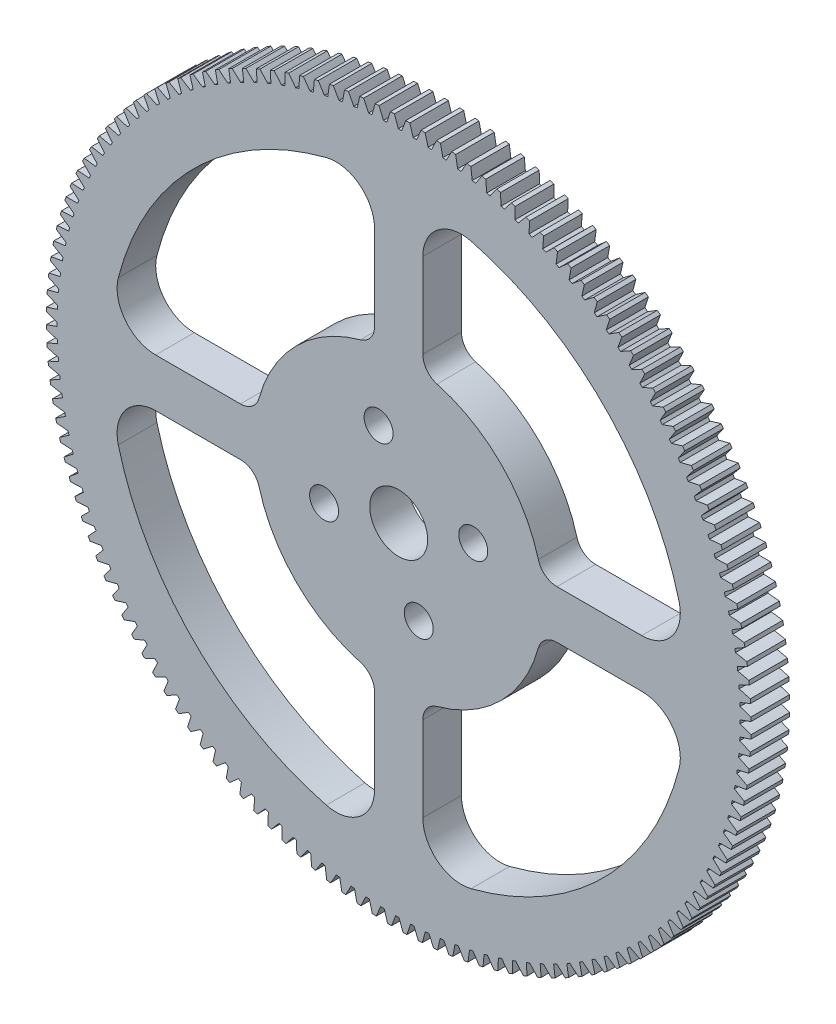
SolidWorks part; units mm, degrees
ref_plane "前视基准面" through (0, 0, 0) normal (0, 0, 1) x (1, 0, 0)
ref_plane "上视基准面" through (0, 0, 0) normal (0, 1, 0) x (1, 0, 0)
ref_plane "右视基准面" through (0, 0, 0) normal (1, 0, 0) x (0, 0, -1)
other "Configuration Table"
sketch "草图1" plane through (0, 0, 0) normal (0, 0, 1) x (1, 0, 0)
  line L0 (0, 0) -> (0.5365, 35.996) construction
  line L1 (0, 0) -> (0.9421, 36.4878) construction
  line L2 (0.9421, 36.4878) -> (0, 0) construction
  line L3 (0, 0) -> (1.7378, 36.4586) construction
  circle A0 centre (0, 0) radius 36.5
  circle A2 centre (0, 0) radius 35.375
  circle A3 centre (0, 0) radius 36
  spline S0 degree 4 poles (0, 33.8289) (0.0006, 33.8564) (0.0042, 33.9332) (0.0184, 34.0782) (0.0521, 34.3136) (0.137, 34.748) (0.3121, 35.3976) (0.5621, 36.0984) (0.8766, 36.8241) (1.1858, 37.45) (1.4504, 37.9418) (1.7905, 38.5279) (2.2281, 39.2183) (2.777, 40.0025) (3.4504, 40.868) (4.1781, 41.7158) (4.943, 42.5297) (5.7422, 43.3106) (6.4677, 43.9647) (7.1084, 44.5057) (7.7601, 45.0294) (8.3177, 45.4547) (8.8774, 45.8623) (9.4586, 46.2638) (9.9104, 46.5666) (10.4031, 46.8822) (10.836, 47.1528) (11.4834, 47.5384) (11.8751, 47.762) (12.508, 48.1138) (12.7943, 48.2608) (13.0526, 48.3982) (13.1292, 48.436) (13.1851, 48.4649) (13.2153, 48.4806) knots 0 0 0 0 0 0.005377 0.015084 0.028532 0.04661 0.092111 0.146842 0.174209 0.201575 0.228941 0.256307 0.307035 0.361767 0.4165 0.471232 0.525964 0.580697 0.635429 0.662795 0.690161 0.744894 0.77226 0.799626 0.826992 0.854358 0.881725 0.909091 0.954545 0.977273 0.988636 0.994318 1 1 1 1 1 construction
  spline S1 degree 4 poles (0.3194, 35.3736) (0.3418, 35.4446) (0.4345, 35.7287) (0.5375, 36.0093) (0.6493, 36.2864) (0.7377, 36.4925) knots 0.077505 0.077505 0.077505 0.077505 0.077505 0.092111 0.136079 0.136079 0.136079 0.136079 0.136079
  spline S2 degree 4 poles (1.5064, 35.3429) (1.4877, 35.415) (1.4098, 35.7035) (1.3214, 35.989) (1.224, 36.2716) (1.1464, 36.482) knots 0.077505 0.077505 0.077505 0.077505 0.077505 0.092111 0.136079 0.136079 0.136079 0.136079 0.136079
  spline S3 degree 4 poles (1.862, 35.326) (1.8875, 35.396) (1.9925, 35.6757) (2.1077, 35.9515) (2.2315, 36.2236) (2.3288, 36.4256) knots 0.077505 0.077505 0.077505 0.077505 0.077505 0.092111 0.136079 0.136079 0.136079 0.136079 0.136079
  dimension "D1" = 72
  dimension "D2" = 73
  dimension "D3" = 70.75
  dimension "D5" = 0.625
  dimension "D6" = 1.875
sketch "草图2" plane through (0, 0, 0) normal (0, 0, 1) x (1, 0, 0)
  circle A0 centre (0, 0) radius 35.375 construction
  circle A1 centre (0, 0) radius 36.5 construction
  arc A2 (1.862, 35.326) -> (1.5064, 35.3429) centre (0, 0) ccw
  arc A3 (1.1464, 36.482) -> (0.7377, 36.4925) centre (0, 0) ccw
  arc A4 (2.7366, 36.3973) -> (2.3288, 36.4256) centre (0, 0) ccw
  arc A5 (3.4012, 35.2111) -> (3.0466, 35.2436) centre (0, 0) ccw
  arc A6 (4.3216, 36.2433) -> (3.9154, 36.2894) centre (0, 0) ccw
  arc A7 (4.9338, 35.0292) -> (4.581, 35.0771) centre (0, 0) ccw
  arc A8 (5.8984, 36.0203) -> (5.4946, 36.0841) centre (0, 0) ccw
  arc A9 (6.4571, 34.7807) -> (6.1067, 34.8439) centre (0, 0) ccw
  arc A10 (7.464, 35.7287) -> (7.0634, 35.81) centre (0, 0) ccw
  arc A11 (7.968, 34.4659) -> (7.6208, 34.5444) centre (0, 0) ccw
  arc A12 (9.0153, 35.3691) -> (8.6187, 35.4679) centre (0, 0) ccw
  arc A13 (9.4638, 34.0856) -> (9.1203, 34.1791) centre (0, 0) ccw
  arc A14 (10.5495, 34.9422) -> (10.1575, 35.0582) centre (0, 0) ccw
  arc A15 (10.9416, 33.6403) -> (10.6025, 33.7487) centre (0, 0) ccw
  arc A16 (12.0637, 34.4488) -> (11.6771, 34.5817) centre (0, 0) ccw
  arc A17 (12.3986, 33.131) -> (12.0645, 33.2541) centre (0, 0) ccw
  arc A18 (13.5548, 33.8898) -> (13.1744, 34.0395) centre (0, 0) ccw
  arc A19 (13.8319, 32.5587) -> (13.5036, 32.6962) centre (0, 0) ccw
  arc A20 (15.0202, 33.2663) -> (14.6466, 33.4324) centre (0, 0) ccw
  arc A21 (15.2389, 31.9244) -> (14.9169, 32.0761) centre (0, 0) ccw
  arc A22 (16.4569, 32.5794) -> (16.091, 32.7617) centre (0, 0) ccw
  arc A23 (16.617, 31.2293) -> (16.3018, 31.3949) centre (0, 0) ccw
  arc A24 (17.8624, 31.8306) -> (17.5047, 32.0286) centre (0, 0) ccw
  arc A25 (17.9634, 30.4747) -> (17.6558, 30.654) centre (0, 0) ccw
  arc A26 (19.2338, 31.0211) -> (18.8851, 31.2346) centre (0, 0) ccw
  arc A27 (19.2755, 29.6622) -> (18.9761, 29.8546) centre (0, 0) ccw
  arc A28 (20.5686, 30.1527) -> (20.2296, 30.3811) centre (0, 0) ccw
  arc A29 (20.551, 28.7931) -> (20.2602, 28.9985) centre (0, 0) ccw
  arc A30 (21.8643, 29.2268) -> (21.5356, 29.4698) centre (0, 0) ccw
  arc A31 (21.7874, 27.8693) -> (21.5059, 28.0872) centre (0, 0) ccw
  arc A32 (23.1183, 28.2452) -> (22.8005, 28.5024) centre (0, 0) ccw
  arc A33 (22.9823, 26.8924) -> (22.7105, 27.1224) centre (0, 0) ccw
  arc A34 (24.3283, 27.21) -> (24.0221, 27.4807) centre (0, 0) ccw
  arc A35 (24.1335, 25.8644) -> (23.872, 26.1059) centre (0, 0) ccw
  arc A36 (25.4921, 26.1229) -> (25.1979, 26.4067) centre (0, 0) ccw
  arc A37 (25.2387, 24.7871) -> (24.988, 25.0398) centre (0, 0) ccw
  arc A38 (26.6073, 24.9861) -> (26.3258, 25.2825) centre (0, 0) ccw
  arc A39 (26.2959, 23.6626) -> (26.0564, 23.926) centre (0, 0) ccw
  arc A40 (27.6718, 23.8017) -> (27.4035, 24.1101) centre (0, 0) ccw
  arc A41 (27.303, 22.493) -> (27.0753, 22.7667) centre (0, 0) ccw
  arc A42 (28.6837, 22.572) -> (28.4291, 22.8918) centre (0, 0) ccw
  arc A43 (28.2581, 21.2807) -> (28.0426, 21.564) centre (0, 0) ccw
  arc A44 (29.641, 21.2994) -> (29.4006, 21.63) centre (0, 0) ccw
  arc A45 (29.1595, 20.0278) -> (28.9565, 20.3203) centre (0, 0) ccw
  arc A46 (30.5418, 19.9862) -> (30.3161, 20.327) centre (0, 0) ccw
  arc A47 (30.0053, 18.7369) -> (29.8153, 19.0379) centre (0, 0) ccw
  arc A48 (31.3845, 18.6349) -> (31.1739, 18.9853) centre (0, 0) ccw
  arc A49 (30.7941, 17.4102) -> (30.6173, 17.7192) centre (0, 0) ccw
  arc A50 (32.1675, 17.2482) -> (31.9723, 17.6074) centre (0, 0) ccw
  arc A51 (31.5242, 16.0504) -> (31.3611, 16.3669) centre (0, 0) ccw
  arc A52 (32.8893, 15.8287) -> (32.7099, 16.196) centre (0, 0) ccw
  arc A53 (32.1943, 14.6601) -> (32.0451, 14.9833) centre (0, 0) ccw
  arc A54 (33.5484, 14.379) -> (33.3852, 14.7538) centre (0, 0) ccw
  arc A55 (32.8031, 13.2418) -> (32.6682, 13.5713) centre (0, 0) ccw
  arc A56 (34.1437, 12.9019) -> (33.997, 13.2835) centre (0, 0) ccw
  arc A57 (33.3495, 11.7984) -> (33.2291, 12.1334) centre (0, 0) ccw
  arc A58 (34.6739, 11.4003) -> (34.5441, 11.788) centre (0, 0) ccw
  arc A59 (33.8324, 10.3325) -> (33.7267, 10.6724) centre (0, 0) ccw
  arc A60 (35.1382, 9.877) -> (35.0254, 10.27) centre (0, 0) ccw
  arc A61 (34.2509, 8.8469) -> (34.1601, 9.1911) centre (0, 0) ccw
  arc A62 (35.5356, 8.3349) -> (35.44, 8.7324) centre (0, 0) ccw
  arc A63 (34.6042, 7.3445) -> (34.5285, 7.6923) centre (0, 0) ccw
  arc A64 (35.8653, 6.7769) -> (35.7872, 7.1782) centre (0, 0) ccw
  arc A65 (34.8916, 5.828) -> (34.8312, 6.1789) centre (0, 0) ccw
  arc A66 (36.1268, 5.2061) -> (36.0662, 5.6104) centre (0, 0) ccw
  arc A67 (35.1126, 4.3006) -> (35.0676, 4.6537) centre (0, 0) ccw
  arc A68 (36.3195, 3.6253) -> (36.2766, 4.0318) centre (0, 0) ccw
  arc A69 (35.2668, 2.7649) -> (35.2372, 3.1196) centre (0, 0) ccw
  arc A70 (36.4431, 2.0376) -> (36.418, 2.4456) centre (0, 0) ccw
  arc A71 (35.3538, 1.2239) -> (35.3397, 1.5796) centre (0, 0) ccw
  arc A72 (36.4973, 0.446) -> (36.49, 0.8548) centre (0, 0) ccw
  arc A73 (35.3736, -0.3194) -> (35.375, 0.0366) centre (0, 0) ccw
  arc A74 (36.482, -1.1464) -> (36.4925, -0.7377) centre (0, 0) ccw
  arc A75 (35.326, -1.862) -> (35.3429, -1.5064) centre (0, 0) ccw
  arc A76 (36.3973, -2.7366) -> (36.4256, -2.3288) centre (0, 0) ccw
  arc A77 (35.2111, -3.4012) -> (35.2436, -3.0466) centre (0, 0) ccw
  arc A78 (36.2433, -4.3216) -> (36.2894, -3.9154) centre (0, 0) ccw
  arc A79 (35.0292, -4.9338) -> (35.0771, -4.581) centre (0, 0) ccw
  arc A80 (36.0203, -5.8984) -> (36.0841, -5.4946) centre (0, 0) ccw
  arc A81 (34.7807, -6.4571) -> (34.8439, -6.1067) centre (0, 0) ccw
  arc A82 (35.7287, -7.464) -> (35.81, -7.0634) centre (0, 0) ccw
  arc A83 (34.4659, -7.968) -> (34.5444, -7.6208) centre (0, 0) ccw
  arc A84 (35.3691, -9.0153) -> (35.4679, -8.6187) centre (0, 0) ccw
  arc A85 (34.0856, -9.4638) -> (34.1791, -9.1203) centre (0, 0) ccw
  arc A86 (34.9422, -10.5495) -> (35.0582, -10.1575) centre (0, 0) ccw
  arc A87 (33.6403, -10.9416) -> (33.7487, -10.6025) centre (0, 0) ccw
  arc A88 (34.4488, -12.0637) -> (34.5817, -11.6771) centre (0, 0) ccw
  arc A89 (33.131, -12.3986) -> (33.2541, -12.0645) centre (0, 0) ccw
  arc A90 (33.8898, -13.5548) -> (34.0395, -13.1744) centre (0, 0) ccw
  arc A91 (32.5587, -13.8319) -> (32.6962, -13.5036) centre (0, 0) ccw
  arc A92 (33.2663, -15.0202) -> (33.4324, -14.6466) centre (0, 0) ccw
  arc A93 (31.9244, -15.2389) -> (32.0761, -14.9169) centre (0, 0) ccw
  arc A94 (32.5794, -16.4569) -> (32.7617, -16.091) centre (0, 0) ccw
  arc A95 (31.2293, -16.617) -> (31.3949, -16.3018) centre (0, 0) ccw
  arc A96 (31.8306, -17.8624) -> (32.0286, -17.5047) centre (0, 0) ccw
  arc A97 (30.4747, -17.9634) -> (30.654, -17.6558) centre (0, 0) ccw
  arc A98 (31.0211, -19.2338) -> (31.2346, -18.8851) centre (0, 0) ccw
  arc A99 (29.6622, -19.2755) -> (29.8546, -18.9761) centre (0, 0) ccw
  arc A100 (30.1527, -20.5686) -> (30.3811, -20.2296) centre (0, 0) ccw
  arc A101 (28.7931, -20.551) -> (28.9985, -20.2602) centre (0, 0) ccw
  arc A102 (29.2268, -21.8643) -> (29.4698, -21.5356) centre (0, 0) ccw
  arc A103 (27.8693, -21.7874) -> (28.0872, -21.5059) centre (0, 0) ccw
  arc A104 (28.2452, -23.1183) -> (28.5024, -22.8005) centre (0, 0) ccw
  arc A105 (26.8924, -22.9823) -> (27.1224, -22.7105) centre (0, 0) ccw
  arc A106 (27.21, -24.3283) -> (27.4807, -24.0221) centre (0, 0) ccw
  arc A107 (25.8644, -24.1335) -> (26.1059, -23.872) centre (0, 0) ccw
  arc A108 (26.1229, -25.4921) -> (26.4067, -25.1979) centre (0, 0) ccw
  arc A109 (24.7871, -25.2387) -> (25.0398, -24.988) centre (0, 0) ccw
  arc A110 (24.9861, -26.6073) -> (25.2825, -26.3258) centre (0, 0) ccw
  arc A111 (23.6626, -26.2959) -> (23.926, -26.0564) centre (0, 0) ccw
  arc A112 (23.8017, -27.6718) -> (24.1101, -27.4035) centre (0, 0) ccw
  arc A113 (22.493, -27.303) -> (22.7667, -27.0753) centre (0, 0) ccw
  arc A114 (22.572, -28.6837) -> (22.8918, -28.4291) centre (0, 0) ccw
  arc A115 (21.2807, -28.2581) -> (21.564, -28.0426) centre (0, 0) ccw
  arc A116 (21.2994, -29.641) -> (21.63, -29.4006) centre (0, 0) ccw
  arc A117 (20.0278, -29.1595) -> (20.3203, -28.9565) centre (0, 0) ccw
  arc A118 (19.9862, -30.5418) -> (20.327, -30.3161) centre (0, 0) ccw
  arc A119 (18.7369, -30.0053) -> (19.0379, -29.8153) centre (0, 0) ccw
  arc A120 (18.6349, -31.3845) -> (18.9853, -31.1739) centre (0, 0) ccw
  arc A121 (17.4102, -30.7941) -> (17.7192, -30.6173) centre (0, 0) ccw
  arc A122 (17.2482, -32.1675) -> (17.6074, -31.9723) centre (0, 0) ccw
  arc A123 (16.0504, -31.5242) -> (16.3669, -31.3611) centre (0, 0) ccw
  arc A124 (15.8287, -32.8893) -> (16.196, -32.7099) centre (0, 0) ccw
  arc A125 (14.6601, -32.1943) -> (14.9833, -32.0451) centre (0, 0) ccw
  arc A126 (14.379, -33.5484) -> (14.7538, -33.3852) centre (0, 0) ccw
  arc A127 (13.2418, -32.8031) -> (13.5713, -32.6682) centre (0, 0) ccw
  arc A128 (12.9019, -34.1437) -> (13.2835, -33.997) centre (0, 0) ccw
  arc A129 (11.7984, -33.3495) -> (12.1334, -33.2291) centre (0, 0) ccw
  arc A130 (11.4003, -34.6739) -> (11.788, -34.5441) centre (0, 0) ccw
  arc A131 (10.3325, -33.8324) -> (10.6724, -33.7267) centre (0, 0) ccw
  arc A132 (9.877, -35.1382) -> (10.27, -35.0254) centre (0, 0) ccw
  arc A133 (8.8469, -34.2509) -> (9.1911, -34.1601) centre (0, 0) ccw
  arc A134 (8.3349, -35.5356) -> (8.7324, -35.44) centre (0, 0) ccw
  arc A135 (7.3445, -34.6042) -> (7.6923, -34.5285) centre (0, 0) ccw
  arc A136 (6.7769, -35.8653) -> (7.1782, -35.7872) centre (0, 0) ccw
  arc A137 (5.828, -34.8916) -> (6.1789, -34.8312) centre (0, 0) ccw
  arc A138 (5.2061, -36.1268) -> (5.6104, -36.0662) centre (0, 0) ccw
  arc A139 (4.3006, -35.1126) -> (4.6537, -35.0676) centre (0, 0) ccw
  arc A140 (3.6253, -36.3195) -> (4.0318, -36.2766) centre (0, 0) ccw
  arc A141 (2.7649, -35.2668) -> (3.1196, -35.2372) centre (0, 0) ccw
  arc A142 (2.0376, -36.4431) -> (2.4456, -36.418) centre (0, 0) ccw
  arc A143 (1.2239, -35.3538) -> (1.5796, -35.3397) centre (0, 0) ccw
  arc A144 (0.446, -36.4973) -> (0.8548, -36.49) centre (0, 0) ccw
  arc A145 (-0.3194, -35.3736) -> (0.0366, -35.375) centre (0, 0) ccw
  arc A146 (-1.1464, -36.482) -> (-0.7377, -36.4925) centre (0, 0) ccw
  arc A147 (-1.862, -35.326) -> (-1.5064, -35.3429) centre (0, 0) ccw
  arc A148 (-2.7366, -36.3973) -> (-2.3288, -36.4256) centre (0, 0) ccw
  arc A149 (-3.4012, -35.2111) -> (-3.0466, -35.2436) centre (0, 0) ccw
  arc A150 (-4.3216, -36.2433) -> (-3.9154, -36.2894) centre (0, 0) ccw
  arc A151 (-4.9338, -35.0292) -> (-4.581, -35.0771) centre (0, 0) ccw
  arc A152 (-5.8984, -36.0203) -> (-5.4946, -36.0841) centre (0, 0) ccw
  arc A153 (-6.4571, -34.7807) -> (-6.1067, -34.8439) centre (0, 0) ccw
  arc A154 (-7.464, -35.7287) -> (-7.0634, -35.81) centre (0, 0) ccw
  arc A155 (-7.968, -34.4659) -> (-7.6208, -34.5444) centre (0, 0) ccw
  arc A156 (-9.0153, -35.3691) -> (-8.6187, -35.4679) centre (0, 0) ccw
  arc A157 (-9.4638, -34.0856) -> (-9.1203, -34.1791) centre (0, 0) ccw
  arc A158 (-10.5495, -34.9422) -> (-10.1575, -35.0582) centre (0, 0) ccw
  arc A159 (-10.9416, -33.6403) -> (-10.6025, -33.7487) centre (0, 0) ccw
  arc A160 (-12.0637, -34.4488) -> (-11.6771, -34.5817) centre (0, 0) ccw
  arc A161 (-12.3986, -33.131) -> (-12.0645, -33.2541) centre (0, 0) ccw
  arc A162 (-13.5548, -33.8898) -> (-13.1744, -34.0395) centre (0, 0) ccw
  arc A163 (-13.8319, -32.5587) -> (-13.5036, -32.6962) centre (0, 0) ccw
  arc A164 (-15.0202, -33.2663) -> (-14.6466, -33.4324) centre (0, 0) ccw
  arc A165 (-15.2389, -31.9244) -> (-14.9169, -32.0761) centre (0, 0) ccw
  arc A166 (-16.4569, -32.5794) -> (-16.091, -32.7617) centre (0, 0) ccw
  arc A167 (-16.617, -31.2293) -> (-16.3018, -31.3949) centre (0, 0) ccw
  arc A168 (-17.8624, -31.8306) -> (-17.5047, -32.0286) centre (0, 0) ccw
  arc A169 (-17.9634, -30.4747) -> (-17.6558, -30.654) centre (0, 0) ccw
  arc A170 (-19.2338, -31.0211) -> (-18.8851, -31.2346) centre (0, 0) ccw
  arc A171 (-19.2755, -29.6622) -> (-18.9761, -29.8546) centre (0, 0) ccw
  arc A172 (-20.5686, -30.1527) -> (-20.2296, -30.3811) centre (0, 0) ccw
  arc A173 (-20.551, -28.7931) -> (-20.2602, -28.9985) centre (0, 0) ccw
  arc A174 (-21.8643, -29.2268) -> (-21.5356, -29.4698) centre (0, 0) ccw
  arc A175 (-21.7874, -27.8693) -> (-21.5059, -28.0872) centre (0, 0) ccw
  arc A176 (-23.1183, -28.2452) -> (-22.8005, -28.5024) centre (0, 0) ccw
  arc A177 (-22.9823, -26.8924) -> (-22.7105, -27.1224) centre (0, 0) ccw
  arc A178 (-24.3283, -27.21) -> (-24.0221, -27.4807) centre (0, 0) ccw
  arc A179 (-24.1335, -25.8644) -> (-23.872, -26.1059) centre (0, 0) ccw
  arc A180 (-25.4921, -26.1229) -> (-25.1979, -26.4067) centre (0, 0) ccw
  arc A181 (-25.2387, -24.7871) -> (-24.988, -25.0398) centre (0, 0) ccw
  arc A182 (-26.6073, -24.9861) -> (-26.3258, -25.2825) centre (0, 0) ccw
  arc A183 (-26.2959, -23.6626) -> (-26.0564, -23.926) centre (0, 0) ccw
  arc A184 (-27.6718, -23.8017) -> (-27.4035, -24.1101) centre (0, 0) ccw
  arc A185 (-27.303, -22.493) -> (-27.0753, -22.7667) centre (0, 0) ccw
  arc A186 (-28.6837, -22.572) -> (-28.4291, -22.8918) centre (0, 0) ccw
  arc A187 (-28.2581, -21.2807) -> (-28.0426, -21.564) centre (0, 0) ccw
  arc A188 (-29.641, -21.2994) -> (-29.4006, -21.63) centre (0, 0) ccw
  arc A189 (-29.1595, -20.0278) -> (-28.9565, -20.3203) centre (0, 0) ccw
  arc A190 (-30.5418, -19.9862) -> (-30.3161, -20.327) centre (0, 0) ccw
  arc A191 (-30.0053, -18.7369) -> (-29.8153, -19.0379) centre (0, 0) ccw
  arc A192 (-31.3845, -18.6349) -> (-31.1739, -18.9853) centre (0, 0) ccw
  arc A193 (-30.7941, -17.4102) -> (-30.6173, -17.7192) centre (0, 0) ccw
  arc A194 (-32.1675, -17.2482) -> (-31.9723, -17.6074) centre (0, 0) ccw
  arc A195 (-31.5242, -16.0504) -> (-31.3611, -16.3669) centre (0, 0) ccw
  arc A196 (-32.8893, -15.8287) -> (-32.7099, -16.196) centre (0, 0) ccw
  arc A197 (-32.1943, -14.6601) -> (-32.0451, -14.9833) centre (0, 0) ccw
  arc A198 (-33.5484, -14.379) -> (-33.3852, -14.7538) centre (0, 0) ccw
  arc A199 (-32.8031, -13.2418) -> (-32.6682, -13.5713) centre (0, 0) ccw
  arc A200 (-34.1437, -12.9019) -> (-33.997, -13.2835) centre (0, 0) ccw
  arc A201 (-33.3495, -11.7984) -> (-33.2291, -12.1334) centre (0, 0) ccw
  arc A202 (-34.6739, -11.4003) -> (-34.5441, -11.788) centre (0, 0) ccw
  arc A203 (-33.8324, -10.3325) -> (-33.7267, -10.6724) centre (0, 0) ccw
  arc A204 (-35.1382, -9.877) -> (-35.0254, -10.27) centre (0, 0) ccw
  arc A205 (-34.2509, -8.8469) -> (-34.1601, -9.1911) centre (0, 0) ccw
  arc A206 (-35.5356, -8.3349) -> (-35.44, -8.7324) centre (0, 0) ccw
  arc A207 (-34.6042, -7.3445) -> (-34.5285, -7.6923) centre (0, 0) ccw
  arc A208 (-35.8653, -6.7769) -> (-35.7872, -7.1782) centre (0, 0) ccw
  arc A209 (-34.8916, -5.828) -> (-34.8312, -6.1789) centre (0, 0) ccw
  arc A210 (-36.1268, -5.2061) -> (-36.0662, -5.6104) centre (0, 0) ccw
  arc A211 (-35.1126, -4.3006) -> (-35.0676, -4.6537) centre (0, 0) ccw
  arc A212 (-36.3195, -3.6253) -> (-36.2766, -4.0318) centre (0, 0) ccw
  arc A213 (-35.2668, -2.7649) -> (-35.2372, -3.1196) centre (0, 0) ccw
  arc A214 (-36.4431, -2.0376) -> (-36.418, -2.4456) centre (0, 0) ccw
  arc A215 (-35.3538, -1.2239) -> (-35.3397, -1.5796) centre (0, 0) ccw
  arc A216 (-36.4973, -0.446) -> (-36.49, -0.8548) centre (0, 0) ccw
  arc A217 (-35.3736, 0.3194) -> (-35.375, -0.0366) centre (0, 0) ccw
  arc A218 (-36.482, 1.1464) -> (-36.4925, 0.7377) centre (0, 0) ccw
  arc A219 (-35.326, 1.862) -> (-35.3429, 1.5064) centre (0, 0) ccw
  arc A220 (-36.3973, 2.7366) -> (-36.4256, 2.3288) centre (0, 0) ccw
  arc A221 (-35.2111, 3.4012) -> (-35.2436, 3.0466) centre (0, 0) ccw
  arc A222 (-36.2433, 4.3216) -> (-36.2894, 3.9154) centre (0, 0) ccw
  arc A223 (-35.0292, 4.9338) -> (-35.0771, 4.581) centre (0, 0) ccw
  arc A224 (-36.0203, 5.8984) -> (-36.0841, 5.4946) centre (0, 0) ccw
  arc A225 (-34.7807, 6.4571) -> (-34.8439, 6.1067) centre (0, 0) ccw
  arc A226 (-35.7287, 7.464) -> (-35.81, 7.0634) centre (0, 0) ccw
  arc A227 (-34.4659, 7.968) -> (-34.5444, 7.6208) centre (0, 0) ccw
  arc A228 (-35.3691, 9.0153) -> (-35.4679, 8.6187) centre (0, 0) ccw
  arc A229 (-34.0856, 9.4638) -> (-34.1791, 9.1203) centre (0, 0) ccw
  arc A230 (-34.9422, 10.5495) -> (-35.0582, 10.1575) centre (0, 0) ccw
  arc A231 (-33.6403, 10.9416) -> (-33.7487, 10.6025) centre (0, 0) ccw
  arc A232 (-34.4488, 12.0637) -> (-34.5817, 11.6771) centre (0, 0) ccw
  arc A233 (-33.131, 12.3986) -> (-33.2541, 12.0645) centre (0, 0) ccw
  arc A234 (-33.8898, 13.5548) -> (-34.0395, 13.1744) centre (0, 0) ccw
  arc A235 (-32.5587, 13.8319) -> (-32.6962, 13.5036) centre (0, 0) ccw
  arc A236 (-33.2663, 15.0202) -> (-33.4324, 14.6466) centre (0, 0) ccw
  arc A237 (-31.9244, 15.2389) -> (-32.0761, 14.9169) centre (0, 0) ccw
  arc A238 (-32.5794, 16.4569) -> (-32.7617, 16.091) centre (0, 0) ccw
  arc A239 (-31.2293, 16.617) -> (-31.3949, 16.3018) centre (0, 0) ccw
  arc A240 (-31.8306, 17.8624) -> (-32.0286, 17.5047) centre (0, 0) ccw
  arc A241 (-30.4747, 17.9634) -> (-30.654, 17.6558) centre (0, 0) ccw
  arc A242 (-31.0211, 19.2338) -> (-31.2346, 18.8851) centre (0, 0) ccw
  arc A243 (-29.6622, 19.2755) -> (-29.8546, 18.9761) centre (0, 0) ccw
  arc A244 (-30.1527, 20.5686) -> (-30.3811, 20.2296) centre (0, 0) ccw
  arc A245 (-28.7931, 20.551) -> (-28.9985, 20.2602) centre (0, 0) ccw
  arc A246 (-29.2268, 21.8643) -> (-29.4698, 21.5356) centre (0, 0) ccw
  arc A247 (-27.8693, 21.7874) -> (-28.0872, 21.5059) centre (0, 0) ccw
  arc A248 (-28.2452, 23.1183) -> (-28.5024, 22.8005) centre (0, 0) ccw
  arc A249 (-26.8924, 22.9823) -> (-27.1224, 22.7105) centre (0, 0) ccw
  arc A250 (-27.21, 24.3283) -> (-27.4807, 24.0221) centre (0, 0) ccw
  arc A251 (-25.8644, 24.1335) -> (-26.1059, 23.872) centre (0, 0) ccw
  arc A252 (-26.1229, 25.4921) -> (-26.4067, 25.1979) centre (0, 0) ccw
  arc A253 (-24.7871, 25.2387) -> (-25.0398, 24.988) centre (0, 0) ccw
  arc A254 (-24.9861, 26.6073) -> (-25.2825, 26.3258) centre (0, 0) ccw
  arc A255 (-23.6626, 26.2959) -> (-23.926, 26.0564) centre (0, 0) ccw
  arc A256 (-23.8017, 27.6718) -> (-24.1101, 27.4035) centre (0, 0) ccw
  arc A257 (-22.493, 27.303) -> (-22.7667, 27.0753) centre (0, 0) ccw
  arc A258 (-22.572, 28.6837) -> (-22.8918, 28.4291) centre (0, 0) ccw
  arc A259 (-21.2807, 28.2581) -> (-21.564, 28.0426) centre (0, 0) ccw
  arc A260 (-21.2994, 29.641) -> (-21.63, 29.4006) centre (0, 0) ccw
  arc A261 (-20.0278, 29.1595) -> (-20.3203, 28.9565) centre (0, 0) ccw
  arc A262 (-19.9862, 30.5418) -> (-20.327, 30.3161) centre (0, 0) ccw
  arc A263 (-18.7369, 30.0053) -> (-19.0379, 29.8153) centre (0, 0) ccw
  arc A264 (-18.6349, 31.3845) -> (-18.9853, 31.1739) centre (0, 0) ccw
  arc A265 (-17.4102, 30.7941) -> (-17.7192, 30.6173) centre (0, 0) ccw
  arc A266 (-17.2482, 32.1675) -> (-17.6074, 31.9723) centre (0, 0) ccw
  arc A267 (-16.0504, 31.5242) -> (-16.3669, 31.3611) centre (0, 0) ccw
  arc A268 (-15.8287, 32.8893) -> (-16.196, 32.7099) centre (0, 0) ccw
  arc A269 (-14.6601, 32.1943) -> (-14.9833, 32.0451) centre (0, 0) ccw
  arc A270 (-14.379, 33.5484) -> (-14.7538, 33.3852) centre (0, 0) ccw
  arc A271 (-13.2418, 32.8031) -> (-13.5713, 32.6682) centre (0, 0) ccw
  arc A272 (-12.9019, 34.1437) -> (-13.2835, 33.997) centre (0, 0) ccw
  arc A273 (-11.7984, 33.3495) -> (-12.1334, 33.2291) centre (0, 0) ccw
  arc A274 (-11.4003, 34.6739) -> (-11.788, 34.5441) centre (0, 0) ccw
  arc A275 (-10.3325, 33.8324) -> (-10.6724, 33.7267) centre (0, 0) ccw
  arc A276 (-9.877, 35.1382) -> (-10.27, 35.0254) centre (0, 0) ccw
  arc A277 (-8.8469, 34.2509) -> (-9.1911, 34.1601) centre (0, 0) ccw
  arc A278 (-8.3349, 35.5356) -> (-8.7324, 35.44) centre (0, 0) ccw
  arc A279 (-7.3445, 34.6042) -> (-7.6923, 34.5285) centre (0, 0) ccw
  arc A280 (-6.7769, 35.8653) -> (-7.1782, 35.7872) centre (0, 0) ccw
  arc A281 (-5.828, 34.8916) -> (-6.1789, 34.8312) centre (0, 0) ccw
  arc A282 (-5.2061, 36.1268) -> (-5.6104, 36.0662) centre (0, 0) ccw
  arc A283 (-4.3006, 35.1126) -> (-4.6537, 35.0676) centre (0, 0) ccw
  arc A284 (-3.6253, 36.3195) -> (-4.0318, 36.2766) centre (0, 0) ccw
  arc A285 (-2.7649, 35.2668) -> (-3.1196, 35.2372) centre (0, 0) ccw
  arc A286 (-2.0376, 36.4431) -> (-2.4456, 36.418) centre (0, 0) ccw
  arc A287 (-1.2239, 35.3538) -> (-1.5796, 35.3397) centre (0, 0) ccw
  arc A288 (-0.446, 36.4973) -> (-0.8548, 36.49) centre (0, 0) ccw
  arc A289 (0.3194, 35.3736) -> (-0.0366, 35.375) centre (0, 0) ccw
  circle A290 centre (0, 0) radius 3
  spline S1 degree 4 poles (-3995.3868, 177.2591) (-83.2794, -0.3115) (111.7377, 33.3623) (-123.1686, 61.6176) (105.0381, 49.2828) (-3991.8271, 268.5989) knots -1.852278 -1.852278 -1.852278 -1.852278 -1.852278 0.092111 2.943504 2.943504 2.943504 2.943504 2.943504 only from (1.5064, 35.3429) to (1.1464, 36.482) construction
  spline S2 degree 4 poles (3999.2107, -29.1483) (83.1524, -4.6085) (-109.8673, 39.0838) (126.1841, 55.1797) (-102.355, 54.6374) (4000.3692, 62.2535) knots -1.852278 -1.852278 -1.852278 -1.852278 -1.852278 0.092111 2.943504 2.943504 2.943504 2.943504 2.943504 only from (0.3194, 35.3736) to (0.7377, 36.4925) construction
  spline S3 degree 4 poles (1.862, 35.326) (1.8875, 35.396) (1.9925, 35.6757) (2.1077, 35.9515) (2.2315, 36.2236) (2.3288, 36.4256) knots 0.077505 0.077505 0.077505 0.077505 0.077505 0.092111 0.136079 0.136079 0.136079 0.136079 0.136079
  spline S4 degree 4 poles (1.5064, 35.3429) (1.4877, 35.415) (1.4098, 35.7035) (1.3214, 35.989) (1.224, 36.2716) (1.1464, 36.482) knots 0.077505 0.077505 0.077505 0.077505 0.077505 0.092111 0.136079 0.136079 0.136079 0.136079 0.136079
  spline S5 degree 4 poles (0.3194, 35.3736) (0.3418, 35.4446) (0.4345, 35.7287) (0.5375, 36.0093) (0.6493, 36.2864) (0.7377, 36.4925) knots 0.077505 0.077505 0.077505 0.077505 0.077505 0.092111 0.136079 0.136079 0.136079 0.136079 0.136079
  spline S6 degree 4 poles (3.0466, 35.2436) (3.0311, 35.3164) (2.9658, 35.608) (2.8899, 35.8971) (2.805, 36.1837) (2.7366, 36.3973) knots 0.077505 0.077505 0.077505 0.077505 0.077505 0.092111 0.136079 0.136079 0.136079 0.136079 0.136079
  spline S7 degree 4 poles (3.4012, 35.2111) (3.4297, 35.2799) (3.5468, 35.5548) (3.6739, 35.8254) (3.8094, 36.0917) (3.9154, 36.2894) knots 0.077505 0.077505 0.077505 0.077505 0.077505 0.092111 0.136079 0.136079 0.136079 0.136079 0.136079
  spline S8 degree 4 poles (4.581, 35.0771) (4.5687, 35.1506) (4.5162, 35.4447) (4.453, 35.7369) (4.3806, 36.0269) (4.3216, 36.2433) knots 0.077505 0.077505 0.077505 0.077505 0.077505 0.092111 0.136079 0.136079 0.136079 0.136079 0.136079
  spline S9 degree 4 poles (4.9338, 35.0292) (4.9653, 35.0968) (5.0943, 35.3663) (5.2331, 35.631) (5.3801, 35.8912) (5.4946, 36.0841) knots 0.077505 0.077505 0.077505 0.077505 0.077505 0.092111 0.136079 0.136079 0.136079 0.136079 0.136079
  spline S10 degree 4 poles (6.1067, 34.8439) (6.0976, 34.9179) (6.058, 35.214) (6.0076, 35.5087) (5.9479, 35.8015) (5.8984, 36.0203) knots 0.077505 0.077505 0.077505 0.077505 0.077505 0.092111 0.136079 0.136079 0.136079 0.136079 0.136079
  spline S11 degree 4 poles (6.4571, 34.7807) (6.4915, 34.8468) (6.6321, 35.1104) (6.7823, 35.3689) (6.9405, 35.6224) (7.0634, 35.81) knots 0.077505 0.077505 0.077505 0.077505 0.077505 0.092111 0.136079 0.136079 0.136079 0.136079 0.136079
  spline S12 degree 4 poles (7.6208, 34.5444) (7.6148, 34.6186) (7.5882, 34.9163) (7.5507, 35.2128) (7.5039, 35.508) (7.464, 35.7287) knots 0.077505 0.077505 0.077505 0.077505 0.077505 0.092111 0.136079 0.136079 0.136079 0.136079 0.136079
  spline S13 degree 4 poles (7.968, 34.4659) (8.0053, 34.5304) (8.1573, 34.7877) (8.3186, 35.0394) (8.4877, 35.2858) (8.6187, 35.4679) knots 0.077505 0.077505 0.077505 0.077505 0.077505 0.092111 0.136079 0.136079 0.136079 0.136079 0.136079
  spline S14 degree 4 poles (9.1203, 34.1791) (9.1176, 34.2535) (9.104, 34.552) (9.0795, 34.8499) (9.0456, 35.1469) (9.0153, 35.3691) knots 0.077505 0.077505 0.077505 0.077505 0.077505 0.092111 0.136079 0.136079 0.136079 0.136079 0.136079
  spline S15 degree 4 poles (9.4638, 34.0856) (9.5039, 34.1484) (9.6669, 34.3988) (9.8391, 34.6432) (10.0188, 34.8819) (10.1575, 35.0582) knots 0.077505 0.077505 0.077505 0.077505 0.077505 0.092111 0.136079 0.136079 0.136079 0.136079 0.136079
  spline S16 degree 4 poles (10.6025, 33.7487) (10.6031, 33.8232) (10.6025, 34.122) (10.591, 34.4207) (10.5701, 34.7189) (10.5495, 34.9422) knots 0.077505 0.077505 0.077505 0.077505 0.077505 0.092111 0.136079 0.136079 0.136079 0.136079 0.136079
  spline S17 degree 4 poles (10.9416, 33.6403) (10.9844, 33.7013) (11.1582, 33.9444) (11.3408, 34.181) (11.5308, 34.4117) (11.6771, 34.5817) knots 0.077505 0.077505 0.077505 0.077505 0.077505 0.092111 0.136079 0.136079 0.136079 0.136079 0.136079
  spline S18 degree 4 poles (12.0645, 33.2541) (12.0683, 33.3285) (12.0808, 33.6271) (12.0823, 33.926) (12.0744, 34.2248) (12.0637, 34.4488) knots 0.077505 0.077505 0.077505 0.077505 0.077505 0.092111 0.136079 0.136079 0.136079 0.136079 0.136079
  spline S19 degree 4 poles (12.3986, 33.131) (12.4439, 33.1901) (12.6282, 33.4254) (12.821, 33.6538) (13.0208, 33.876) (13.1744, 34.0395) knots 0.077505 0.077505 0.077505 0.077505 0.077505 0.092111 0.136079 0.136079 0.136079 0.136079 0.136079
  spline S20 degree 4 poles (13.5036, 32.6962) (13.5106, 32.7704) (13.5361, 33.0681) (13.5506, 33.3667) (13.5558, 33.6655) (13.5548, 33.8898) knots 0.077505 0.077505 0.077505 0.077505 0.077505 0.092111 0.136079 0.136079 0.136079 0.136079 0.136079
  spline S21 degree 4 poles (13.8319, 32.5587) (13.8798, 32.6157) (14.0742, 32.8427) (14.2768, 33.0625) (14.4861, 33.2758) (14.6466, 33.4324) knots 0.077505 0.077505 0.077505 0.077505 0.077505 0.092111 0.136079 0.136079 0.136079 0.136079 0.136079
  spline S22 degree 4 poles (14.9169, 32.0761) (14.9272, 32.1499) (14.9656, 32.4462) (14.9932, 32.7439) (15.0114, 33.0422) (15.0202, 33.2663) knots 0.077505 0.077505 0.077505 0.077505 0.077505 0.092111 0.136079 0.136079 0.136079 0.136079 0.136079
  spline S23 degree 4 poles (15.2389, 31.9244) (15.2893, 31.9793) (15.4934, 32.1975) (15.7053, 32.4083) (15.9238, 32.6123) (16.091, 32.7617) knots 0.077505 0.077505 0.077505 0.077505 0.077505 0.092111 0.136079 0.136079 0.136079 0.136079 0.136079
  spline S24 degree 4 poles (16.3018, 31.3949) (16.3153, 31.4682) (16.3666, 31.7625) (16.4072, 32.0587) (16.4384, 32.3559) (16.4569, 32.5794) knots 0.077505 0.077505 0.077505 0.077505 0.077505 0.092111 0.136079 0.136079 0.136079 0.136079 0.136079
  spline S25 degree 4 poles (16.617, 31.2293) (16.6697, 31.2819) (16.883, 31.4911) (17.104, 31.6924) (17.3311, 31.8866) (17.5047, 32.0286) knots 0.077505 0.077505 0.077505 0.077505 0.077505 0.092111 0.136079 0.136079 0.136079 0.136079 0.136079
  spline S26 degree 4 poles (17.6558, 30.654) (17.6724, 30.7266) (17.7365, 31.0184) (17.7899, 31.3125) (17.8341, 31.6081) (17.8624, 31.8306) knots 0.077505 0.077505 0.077505 0.077505 0.077505 0.092111 0.136079 0.136079 0.136079 0.136079 0.136079
  spline S27 degree 4 poles (17.9634, 30.4747) (18.0183, 30.525) (18.2406, 30.7247) (18.4701, 30.9162) (18.7055, 31.1003) (18.8851, 31.2346) knots 0.077505 0.077505 0.077505 0.077505 0.077505 0.092111 0.136079 0.136079 0.136079 0.136079 0.136079
  spline S28 degree 4 poles (18.9761, 29.8546) (18.9959, 29.9265) (19.0727, 30.2152) (19.1388, 30.5067) (19.1958, 30.8001) (19.2338, 31.0211) knots 0.077505 0.077505 0.077505 0.077505 0.077505 0.092111 0.136079 0.136079 0.136079 0.136079 0.136079
  spline S29 degree 4 poles (19.2755, 29.6622) (19.3326, 29.71) (19.5634, 29.8998) (19.8011, 30.0811) (20.0443, 30.2548) (20.2296, 30.3811) knots 0.077505 0.077505 0.077505 0.077505 0.077505 0.092111 0.136079 0.136079 0.136079 0.136079 0.136079
  spline S30 degree 4 poles (20.2602, 28.9985) (20.2832, 29.0694) (20.3725, 29.3545) (20.4513, 29.6429) (20.521, 29.9335) (20.5686, 30.1527) knots 0.077505 0.077505 0.077505 0.077505 0.077505 0.092111 0.136079 0.136079 0.136079 0.136079 0.136079
  spline S31 degree 4 poles (20.551, 28.7931) (20.6102, 28.8385) (20.849, 29.018) (21.0944, 29.1887) (21.3449, 29.3517) (21.5356, 29.4698) knots 0.077505 0.077505 0.077505 0.077505 0.077505 0.092111 0.136079 0.136079 0.136079 0.136079 0.136079
  spline S32 degree 4 poles (21.5059, 28.0872) (21.5319, 28.157) (21.6335, 28.438) (21.7248, 28.7226) (21.8072, 29.0099) (21.8643, 29.2268) knots 0.077505 0.077505 0.077505 0.077505 0.077505 0.092111 0.136079 0.136079 0.136079 0.136079 0.136079
  spline S33 degree 4 poles (21.7874, 27.8693) (21.8485, 27.912) (22.0949, 28.081) (22.3475, 28.2408) (22.6049, 28.3927) (22.8005, 28.5024) knots 0.077505 0.077505 0.077505 0.077505 0.077505 0.092111 0.136079 0.136079 0.136079 0.136079 0.136079
  spline S34 degree 4 poles (22.7105, 27.1224) (22.7396, 27.191) (22.8534, 27.4673) (22.957, 27.7476) (23.0518, 28.031) (23.1183, 28.2452) knots 0.077505 0.077505 0.077505 0.077505 0.077505 0.092111 0.136079 0.136079 0.136079 0.136079 0.136079
  spline S35 degree 4 poles (22.9823, 26.8924) (23.0452, 26.9324) (23.2988, 27.0905) (23.5581, 27.2392) (23.8219, 27.3796) (24.0221, 27.4807) knots 0.077505 0.077505 0.077505 0.077505 0.077505 0.092111 0.136079 0.136079 0.136079 0.136079 0.136079
  spline S36 degree 4 poles (23.872, 26.1059) (23.904, 26.1732) (24.0297, 26.4443) (24.1455, 26.7198) (24.2526, 26.9989) (24.3283, 27.21) knots 0.077505 0.077505 0.077505 0.077505 0.077505 0.092111 0.136079 0.136079 0.136079 0.136079 0.136079
  spline S37 degree 4 poles (24.1335, 25.8644) (24.198, 25.9016) (24.4583, 26.0484) (24.7238, 26.1857) (24.9935, 26.3145) (25.1979, 26.4067) knots 0.077505 0.077505 0.077505 0.077505 0.077505 0.092111 0.136079 0.136079 0.136079 0.136079 0.136079
  spline S38 degree 4 poles (24.988, 25.0398) (25.0229, 25.1056) (25.1603, 25.3709) (25.288, 25.6412) (25.4072, 25.9153) (25.4921, 26.1229) knots 0.077505 0.077505 0.077505 0.077505 0.077505 0.092111 0.136079 0.136079 0.136079 0.136079 0.136079
  spline S39 degree 4 poles (25.2387, 24.7871) (25.3048, 24.8214) (25.5712, 24.9568) (25.8425, 25.0823) (26.1175, 25.1992) (26.3258, 25.2825) knots 0.077505 0.077505 0.077505 0.077505 0.077505 0.092111 0.136079 0.136079 0.136079 0.136079 0.136079
  spline S40 degree 4 poles (26.0564, 23.926) (26.0942, 23.9902) (26.243, 24.2493) (26.3824, 24.5137) (26.5134, 24.7824) (26.6073, 24.9861) knots 0.077505 0.077505 0.077505 0.077505 0.077505 0.092111 0.136079 0.136079 0.136079 0.136079 0.136079
  spline S41 degree 4 poles (26.2959, 23.6626) (26.3634, 23.694) (26.6355, 23.8176) (26.912, 23.9312) (27.1918, 24.036) (27.4035, 24.1101) knots 0.077505 0.077505 0.077505 0.077505 0.077505 0.092111 0.136079 0.136079 0.136079 0.136079 0.136079
  spline S42 degree 4 poles (27.0753, 22.7667) (27.1158, 22.8292) (27.2758, 23.0815) (27.4266, 23.3396) (27.5692, 23.6023) (27.6718, 23.8017) knots 0.077505 0.077505 0.077505 0.077505 0.077505 0.092111 0.136079 0.136079 0.136079 0.136079 0.136079
  spline S43 degree 4 poles (27.303, 22.493) (27.3718, 22.5215) (27.649, 22.6331) (27.9302, 22.7345) (28.2144, 22.8271) (28.4291, 22.8918) knots 0.077505 0.077505 0.077505 0.077505 0.077505 0.092111 0.136079 0.136079 0.136079 0.136079 0.136079
  spline S44 degree 4 poles (28.0426, 21.564) (28.0857, 21.6247) (28.2566, 21.8698) (28.4185, 22.1211) (28.5724, 22.3773) (28.6837, 22.572) knots 0.077505 0.077505 0.077505 0.077505 0.077505 0.092111 0.136079 0.136079 0.136079 0.136079 0.136079
  spline S45 degree 4 poles (28.2581, 21.2807) (28.3282, 21.3061) (28.6099, 21.4055) (28.8953, 21.4946) (29.1832, 21.5746) (29.4006, 21.63) knots 0.077505 0.077505 0.077505 0.077505 0.077505 0.092111 0.136079 0.136079 0.136079 0.136079 0.136079
  spline S46 degree 4 poles (28.9565, 20.3203) (29.0023, 20.379) (29.1837, 20.6164) (29.3564, 20.8604) (29.5213, 21.1097) (29.641, 21.2994) knots 0.077505 0.077505 0.077505 0.077505 0.077505 0.092111 0.136079 0.136079 0.136079 0.136079 0.136079
  spline S47 degree 4 poles (29.1595, 20.0278) (29.2306, 20.0502) (29.5164, 20.1372) (29.8054, 20.2138) (30.0965, 20.2812) (30.3161, 20.327) knots 0.077505 0.077505 0.077505 0.077505 0.077505 0.092111 0.136079 0.136079 0.136079 0.136079 0.136079
  spline S48 degree 4 poles (29.8153, 19.0379) (29.8636, 19.0946) (30.0552, 19.3238) (30.2384, 19.5601) (30.414, 19.8019) (30.5418, 19.9862) knots 0.077505 0.077505 0.077505 0.077505 0.077505 0.092111 0.136079 0.136079 0.136079 0.136079 0.136079
  spline S49 degree 4 poles (30.0053, 18.7369) (30.0773, 18.7561) (30.3667, 18.8306) (30.6587, 18.8944) (30.9525, 18.9491) (31.1739, 18.9853) knots 0.077505 0.077505 0.077505 0.077505 0.077505 0.092111 0.136079 0.136079 0.136079 0.136079 0.136079
  spline S50 degree 4 poles (30.6173, 17.7192) (30.6681, 17.7738) (30.8695, 17.9945) (31.0628, 18.2225) (31.2488, 18.4564) (31.3845, 18.6349) knots 0.077505 0.077505 0.077505 0.077505 0.077505 0.092111 0.136079 0.136079 0.136079 0.136079 0.136079
  spline S51 degree 4 poles (30.7941, 17.4102) (30.8668, 17.4263) (31.1592, 17.4881) (31.4537, 17.5391) (31.7496, 17.5809) (31.9723, 17.6074) knots 0.077505 0.077505 0.077505 0.077505 0.077505 0.092111 0.136079 0.136079 0.136079 0.136079 0.136079
  spline S52 degree 4 poles (31.3611, 16.3669) (31.4142, 16.4191) (31.625, 16.6308) (31.8281, 16.8502) (32.0241, 17.0758) (32.1675, 17.2482) knots 0.077505 0.077505 0.077505 0.077505 0.077505 0.092111 0.136079 0.136079 0.136079 0.136079 0.136079
  spline S53 degree 4 poles (31.5242, 16.0504) (31.5976, 16.0633) (31.8923, 16.1123) (32.1888, 16.1504) (32.4863, 16.1793) (32.7099, 16.196) knots 0.077505 0.077505 0.077505 0.077505 0.077505 0.092111 0.136079 0.136079 0.136079 0.136079 0.136079
  spline S54 degree 4 poles (32.0451, 14.9833) (32.1004, 15.0332) (32.3203, 15.2355) (32.5328, 15.4458) (32.7385, 15.6626) (32.8893, 15.8287) knots 0.077505 0.077505 0.077505 0.077505 0.077505 0.092111 0.136079 0.136079 0.136079 0.136079 0.136079
  spline S55 degree 4 poles (32.1943, 14.6601) (32.2682, 14.6698) (32.5648, 14.7058) (32.8626, 14.731) (33.1611, 14.7468) (33.3852, 14.7538) knots 0.077505 0.077505 0.077505 0.077505 0.077505 0.092111 0.136079 0.136079 0.136079 0.136079 0.136079
  spline S56 degree 4 poles (32.6682, 13.5713) (32.7256, 13.6187) (32.9541, 13.8112) (33.1756, 14.0121) (33.3905, 14.2197) (33.5484, 14.379) knots 0.077505 0.077505 0.077505 0.077505 0.077505 0.092111 0.136079 0.136079 0.136079 0.136079 0.136079
  spline S57 degree 4 poles (32.8031, 13.2418) (32.8773, 13.2483) (33.1752, 13.2714) (33.4739, 13.2835) (33.7728, 13.2863) (33.997, 13.2835) knots 0.077505 0.077505 0.077505 0.077505 0.077505 0.092111 0.136079 0.136079 0.136079 0.136079 0.136079
  spline S58 degree 4 poles (33.2291, 12.1334) (33.2885, 12.1783) (33.5252, 12.3607) (33.7552, 12.5516) (33.979, 12.7497) (34.1437, 12.9019) knots 0.077505 0.077505 0.077505 0.077505 0.077505 0.092111 0.136079 0.136079 0.136079 0.136079 0.136079
  spline S59 degree 4 poles (33.3495, 11.7984) (33.4239, 11.8016) (33.7226, 11.8117) (34.0215, 11.8108) (34.3202, 11.8005) (34.5441, 11.788) knots 0.077505 0.077505 0.077505 0.077505 0.077505 0.092111 0.136079 0.136079 0.136079 0.136079 0.136079
  spline S60 degree 4 poles (33.7267, 10.6724) (33.7881, 10.7147) (34.0325, 10.8865) (34.2705, 11.0673) (34.5028, 11.2554) (34.6739, 11.4003) knots 0.077505 0.077505 0.077505 0.077505 0.077505 0.092111 0.136079 0.136079 0.136079 0.136079 0.136079
  spline S61 degree 4 poles (33.8324, 10.3325) (33.9069, 10.3324) (34.2057, 10.3295) (34.5043, 10.3155) (34.8022, 10.2923) (35.0254, 10.27) knots 0.077505 0.077505 0.077505 0.077505 0.077505 0.092111 0.136079 0.136079 0.136079 0.136079 0.136079
  spline S62 degree 4 poles (34.1601, 9.1911) (34.2233, 9.2307) (34.4749, 9.3917) (34.7207, 9.5619) (34.9609, 9.7397) (35.1382, 9.877) knots 0.077505 0.077505 0.077505 0.077505 0.077505 0.092111 0.136079 0.136079 0.136079 0.136079 0.136079
  spline S63 degree 4 poles (34.2509, 8.8469) (34.3253, 8.8436) (34.6237, 8.8276) (34.9214, 8.8007) (35.218, 8.7644) (35.44, 8.7324) knots 0.077505 0.077505 0.077505 0.077505 0.077505 0.092111 0.136079 0.136079 0.136079 0.136079 0.136079
  spline S64 degree 4 poles (34.5285, 7.6923) (34.5933, 7.7291) (34.8518, 7.879) (35.1047, 8.0383) (35.3525, 8.2055) (35.5356, 8.3349) knots 0.077505 0.077505 0.077505 0.077505 0.077505 0.092111 0.136079 0.136079 0.136079 0.136079 0.136079
  spline S65 degree 4 poles (34.6042, 7.3445) (34.6784, 7.3379) (34.9758, 7.3089) (35.272, 7.269) (35.5668, 7.2199) (35.7872, 7.1782) knots 0.077505 0.077505 0.077505 0.077505 0.077505 0.092111 0.136079 0.136079 0.136079 0.136079 0.136079
  spline S66 degree 4 poles (34.8312, 6.1789) (34.8975, 6.2128) (35.1623, 6.3513) (35.4219, 6.4994) (35.6767, 6.6556) (35.8653, 6.7769) knots 0.077505 0.077505 0.077505 0.077505 0.077505 0.092111 0.136079 0.136079 0.136079 0.136079 0.136079
  spline S67 degree 4 poles (34.8916, 5.828) (34.9655, 5.8183) (35.2613, 5.7763) (35.5555, 5.7236) (35.8479, 5.6616) (36.0662, 5.6104) knots 0.077505 0.077505 0.077505 0.077505 0.077505 0.092111 0.136079 0.136079 0.136079 0.136079 0.136079
  spline S68 degree 4 poles (35.0676, 4.6537) (35.1353, 4.6847) (35.4059, 4.8115) (35.6717, 4.9481) (35.9331, 5.0931) (36.1268, 5.2061) knots 0.077505 0.077505 0.077505 0.077505 0.077505 0.092111 0.136079 0.136079 0.136079 0.136079 0.136079
  spline S69 degree 4 poles (35.1126, 4.3006) (35.186, 4.2876) (35.4797, 4.2328) (35.7714, 4.1672) (36.0607, 4.0926) (36.2766, 4.0318) knots 0.077505 0.077505 0.077505 0.077505 0.077505 0.092111 0.136079 0.136079 0.136079 0.136079 0.136079
  spline S70 degree 4 poles (35.2372, 3.1196) (35.3062, 3.1476) (35.582, 3.2625) (35.8536, 3.3875) (36.121, 3.5208) (36.3195, 3.6253) knots 0.077505 0.077505 0.077505 0.077505 0.077505 0.092111 0.136079 0.136079 0.136079 0.136079 0.136079
  spline S71 degree 4 poles (35.2668, 2.7649) (35.3395, 2.7487) (35.6306, 2.6811) (35.9191, 2.6029) (36.2049, 2.5157) (36.418, 2.4456) knots 0.077505 0.077505 0.077505 0.077505 0.077505 0.092111 0.136079 0.136079 0.136079 0.136079 0.136079
  spline S72 degree 4 poles (35.3397, 1.5796) (35.4099, 1.6046) (35.6905, 1.7073) (35.9672, 1.8203) (36.2402, 1.9419) (36.4431, 2.0376) knots 0.077505 0.077505 0.077505 0.077505 0.077505 0.092111 0.136079 0.136079 0.136079 0.136079 0.136079
  spline S73 degree 4 poles (35.3538, 1.2239) (35.4258, 1.2046) (35.7136, 1.1244) (35.9984, 1.0337) (36.2802, 0.9341) (36.49, 0.8548) knots 0.077505 0.077505 0.077505 0.077505 0.077505 0.092111 0.136079 0.136079 0.136079 0.136079 0.136079
  spline S74 degree 4 poles (35.375, 0.0366) (35.4462, 0.0585) (35.731, 0.1489) (36.0124, 0.2497) (36.2905, 0.3593) (36.4973, 0.446) knots 0.077505 0.077505 0.077505 0.077505 0.077505 0.092111 0.136079 0.136079 0.136079 0.136079 0.136079
  spline S75 degree 4 poles (35.3736, -0.3194) (35.4446, -0.3418) (35.7287, -0.4345) (36.0093, -0.5375) (36.2864, -0.6493) (36.4925, -0.7377) knots 0.077505 0.077505 0.077505 0.077505 0.077505 0.092111 0.136079 0.136079 0.136079 0.136079 0.136079
  spline S76 degree 4 poles (35.3429, -1.5064) (35.415, -1.4877) (35.7035, -1.4098) (35.989, -1.3214) (36.2716, -1.224) (36.482, -1.1464) knots 0.077505 0.077505 0.077505 0.077505 0.077505 0.092111 0.136079 0.136079 0.136079 0.136079 0.136079
  spline S77 degree 4 poles (35.326, -1.862) (35.396, -1.8875) (35.6757, -1.9925) (35.9515, -2.1077) (36.2236, -2.2315) (36.4256, -2.3288) knots 0.077505 0.077505 0.077505 0.077505 0.077505 0.092111 0.136079 0.136079 0.136079 0.136079 0.136079
  spline S78 degree 4 poles (35.2436, -3.0466) (35.3164, -3.0311) (35.608, -2.9658) (35.8971, -2.8899) (36.1837, -2.805) (36.3973, -2.7366) knots 0.077505 0.077505 0.077505 0.077505 0.077505 0.092111 0.136079 0.136079 0.136079 0.136079 0.136079
  spline S79 degree 4 poles (35.2111, -3.4012) (35.2799, -3.4297) (35.5548, -3.5468) (35.8254, -3.6739) (36.0917, -3.8094) (36.2894, -3.9154) knots 0.077505 0.077505 0.077505 0.077505 0.077505 0.092111 0.136079 0.136079 0.136079 0.136079 0.136079
  spline S80 degree 4 poles (35.0771, -4.581) (35.1506, -4.5687) (35.4447, -4.5162) (35.7369, -4.453) (36.0269, -4.3806) (36.2433, -4.3216) knots 0.077505 0.077505 0.077505 0.077505 0.077505 0.092111 0.136079 0.136079 0.136079 0.136079 0.136079
  spline S81 degree 4 poles (35.0292, -4.9338) (35.0968, -4.9653) (35.3663, -5.0943) (35.631, -5.2331) (35.8912, -5.3801) (36.0841, -5.4946) knots 0.077505 0.077505 0.077505 0.077505 0.077505 0.092111 0.136079 0.136079 0.136079 0.136079 0.136079
  spline S82 degree 4 poles (34.8439, -6.1067) (34.9179, -6.0976) (35.214, -6.058) (35.5087, -6.0076) (35.8015, -5.9479) (36.0203, -5.8984) knots 0.077505 0.077505 0.077505 0.077505 0.077505 0.092111 0.136079 0.136079 0.136079 0.136079 0.136079
  spline S83 degree 4 poles (34.7807, -6.4571) (34.8468, -6.4915) (35.1104, -6.6321) (35.3689, -6.7823) (35.6224, -6.9405) (35.81, -7.0634) knots 0.077505 0.077505 0.077505 0.077505 0.077505 0.092111 0.136079 0.136079 0.136079 0.136079 0.136079
  spline S84 degree 4 poles (34.5444, -7.6208) (34.6186, -7.6148) (34.9163, -7.5882) (35.2128, -7.5507) (35.508, -7.5039) (35.7287, -7.464) knots 0.077505 0.077505 0.077505 0.077505 0.077505 0.092111 0.136079 0.136079 0.136079 0.136079 0.136079
  spline S85 degree 4 poles (34.4659, -7.968) (34.5304, -8.0053) (34.7877, -8.1573) (35.0394, -8.3186) (35.2858, -8.4877) (35.4679, -8.6187) knots 0.077505 0.077505 0.077505 0.077505 0.077505 0.092111 0.136079 0.136079 0.136079 0.136079 0.136079
  spline S86 degree 4 poles (34.1791, -9.1203) (34.2535, -9.1176) (34.552, -9.104) (34.8499, -9.0795) (35.1469, -9.0456) (35.3691, -9.0153) knots 0.077505 0.077505 0.077505 0.077505 0.077505 0.092111 0.136079 0.136079 0.136079 0.136079 0.136079
  spline S87 degree 4 poles (34.0856, -9.4638) (34.1484, -9.5039) (34.3988, -9.6669) (34.6432, -9.8391) (34.8819, -10.0188) (35.0582, -10.1575) knots 0.077505 0.077505 0.077505 0.077505 0.077505 0.092111 0.136079 0.136079 0.136079 0.136079 0.136079
  spline S88 degree 4 poles (33.7487, -10.6025) (33.8232, -10.6031) (34.122, -10.6025) (34.4207, -10.591) (34.7189, -10.5701) (34.9422, -10.5495) knots 0.077505 0.077505 0.077505 0.077505 0.077505 0.092111 0.136079 0.136079 0.136079 0.136079 0.136079
  spline S89 degree 4 poles (33.6403, -10.9416) (33.7013, -10.9844) (33.9444, -11.1582) (34.181, -11.3408) (34.4117, -11.5308) (34.5817, -11.6771) knots 0.077505 0.077505 0.077505 0.077505 0.077505 0.092111 0.136079 0.136079 0.136079 0.136079 0.136079
  spline S90 degree 4 poles (33.2541, -12.0645) (33.3285, -12.0683) (33.6271, -12.0808) (33.926, -12.0823) (34.2248, -12.0744) (34.4488, -12.0637) knots 0.077505 0.077505 0.077505 0.077505 0.077505 0.092111 0.136079 0.136079 0.136079 0.136079 0.136079
  spline S91 degree 4 poles (33.131, -12.3986) (33.1901, -12.4439) (33.4254, -12.6282) (33.6538, -12.821) (33.876, -13.0208) (34.0395, -13.1744) knots 0.077505 0.077505 0.077505 0.077505 0.077505 0.092111 0.136079 0.136079 0.136079 0.136079 0.136079
  spline S92 degree 4 poles (32.6962, -13.5036) (32.7704, -13.5106) (33.0681, -13.5361) (33.3667, -13.5506) (33.6655, -13.5558) (33.8898, -13.5548) knots 0.077505 0.077505 0.077505 0.077505 0.077505 0.092111 0.136079 0.136079 0.136079 0.136079 0.136079
  spline S93 degree 4 poles (32.5587, -13.8319) (32.6157, -13.8798) (32.8427, -14.0742) (33.0625, -14.2768) (33.2758, -14.4861) (33.4324, -14.6466) knots 0.077505 0.077505 0.077505 0.077505 0.077505 0.092111 0.136079 0.136079 0.136079 0.136079 0.136079
  spline S94 degree 4 poles (32.0761, -14.9169) (32.1499, -14.9272) (32.4462, -14.9656) (32.7439, -14.9932) (33.0422, -15.0114) (33.2663, -15.0202) knots 0.077505 0.077505 0.077505 0.077505 0.077505 0.092111 0.136079 0.136079 0.136079 0.136079 0.136079
  spline S95 degree 4 poles (31.9244, -15.2389) (31.9793, -15.2893) (32.1975, -15.4934) (32.4083, -15.7053) (32.6123, -15.9238) (32.7617, -16.091) knots 0.077505 0.077505 0.077505 0.077505 0.077505 0.092111 0.136079 0.136079 0.136079 0.136079 0.136079
  spline S96 degree 4 poles (31.3949, -16.3018) (31.4682, -16.3153) (31.7625, -16.3666) (32.0587, -16.4072) (32.3559, -16.4384) (32.5794, -16.4569) knots 0.077505 0.077505 0.077505 0.077505 0.077505 0.092111 0.136079 0.136079 0.136079 0.136079 0.136079
  spline S97 degree 4 poles (31.2293, -16.617) (31.2819, -16.6697) (31.4911, -16.883) (31.6924, -17.104) (31.8866, -17.3311) (32.0286, -17.5047) knots 0.077505 0.077505 0.077505 0.077505 0.077505 0.092111 0.136079 0.136079 0.136079 0.136079 0.136079
  spline S98 degree 4 poles (30.654, -17.6558) (30.7266, -17.6724) (31.0184, -17.7365) (31.3125, -17.7899) (31.6081, -17.8341) (31.8306, -17.8624) knots 0.077505 0.077505 0.077505 0.077505 0.077505 0.092111 0.136079 0.136079 0.136079 0.136079 0.136079
  spline S99 degree 4 poles (30.4747, -17.9634) (30.525, -18.0183) (30.7247, -18.2406) (30.9162, -18.4701) (31.1003, -18.7055) (31.2346, -18.8851) knots 0.077505 0.077505 0.077505 0.077505 0.077505 0.092111 0.136079 0.136079 0.136079 0.136079 0.136079
  spline S100 degree 4 poles (29.8546, -18.9761) (29.9265, -18.9959) (30.2152, -19.0727) (30.5067, -19.1388) (30.8001, -19.1958) (31.0211, -19.2338) knots 0.077505 0.077505 0.077505 0.077505 0.077505 0.092111 0.136079 0.136079 0.136079 0.136079 0.136079
  spline S101 degree 4 poles (29.6622, -19.2755) (29.71, -19.3326) (29.8998, -19.5634) (30.0811, -19.8011) (30.2548, -20.0443) (30.3811, -20.2296) knots 0.077505 0.077505 0.077505 0.077505 0.077505 0.092111 0.136079 0.136079 0.136079 0.136079 0.136079
  spline S102 degree 4 poles (28.9985, -20.2602) (29.0694, -20.2832) (29.3545, -20.3725) (29.6429, -20.4513) (29.9335, -20.521) (30.1527, -20.5686) knots 0.077505 0.077505 0.077505 0.077505 0.077505 0.092111 0.136079 0.136079 0.136079 0.136079 0.136079
  spline S103 degree 4 poles (28.7931, -20.551) (28.8385, -20.6102) (29.018, -20.849) (29.1887, -21.0944) (29.3517, -21.3449) (29.4698, -21.5356) knots 0.077505 0.077505 0.077505 0.077505 0.077505 0.092111 0.136079 0.136079 0.136079 0.136079 0.136079
  spline S104 degree 4 poles (28.0872, -21.5059) (28.157, -21.5319) (28.438, -21.6335) (28.7226, -21.7248) (29.0099, -21.8072) (29.2268, -21.8643) knots 0.077505 0.077505 0.077505 0.077505 0.077505 0.092111 0.136079 0.136079 0.136079 0.136079 0.136079
  spline S105 degree 4 poles (27.8693, -21.7874) (27.912, -21.8485) (28.081, -22.0949) (28.2408, -22.3475) (28.3927, -22.6049) (28.5024, -22.8005) knots 0.077505 0.077505 0.077505 0.077505 0.077505 0.092111 0.136079 0.136079 0.136079 0.136079 0.136079
  spline S106 degree 4 poles (27.1224, -22.7105) (27.191, -22.7396) (27.4673, -22.8534) (27.7476, -22.957) (28.031, -23.0518) (28.2452, -23.1183) knots 0.077505 0.077505 0.077505 0.077505 0.077505 0.092111 0.136079 0.136079 0.136079 0.136079 0.136079
  spline S107 degree 4 poles (26.8924, -22.9823) (26.9324, -23.0452) (27.0905, -23.2988) (27.2392, -23.5581) (27.3796, -23.8219) (27.4807, -24.0221) knots 0.077505 0.077505 0.077505 0.077505 0.077505 0.092111 0.136079 0.136079 0.136079 0.136079 0.136079
  spline S108 degree 4 poles (26.1059, -23.872) (26.1732, -23.904) (26.4443, -24.0297) (26.7198, -24.1455) (26.9989, -24.2526) (27.21, -24.3283) knots 0.077505 0.077505 0.077505 0.077505 0.077505 0.092111 0.136079 0.136079 0.136079 0.136079 0.136079
  spline S109 degree 4 poles (25.8644, -24.1335) (25.9016, -24.198) (26.0484, -24.4583) (26.1857, -24.7238) (26.3145, -24.9935) (26.4067, -25.1979) knots 0.077505 0.077505 0.077505 0.077505 0.077505 0.092111 0.136079 0.136079 0.136079 0.136079 0.136079
  spline S110 degree 4 poles (25.0398, -24.988) (25.1056, -25.0229) (25.3709, -25.1603) (25.6412, -25.288) (25.9153, -25.4072) (26.1229, -25.4921) knots 0.077505 0.077505 0.077505 0.077505 0.077505 0.092111 0.136079 0.136079 0.136079 0.136079 0.136079
  spline S111 degree 4 poles (24.7871, -25.2387) (24.8214, -25.3048) (24.9568, -25.5712) (25.0823, -25.8425) (25.1992, -26.1175) (25.2825, -26.3258) knots 0.077505 0.077505 0.077505 0.077505 0.077505 0.092111 0.136079 0.136079 0.136079 0.136079 0.136079
  spline S112 degree 4 poles (23.926, -26.0564) (23.9902, -26.0942) (24.2493, -26.243) (24.5137, -26.3824) (24.7824, -26.5134) (24.9861, -26.6073) knots 0.077505 0.077505 0.077505 0.077505 0.077505 0.092111 0.136079 0.136079 0.136079 0.136079 0.136079
  spline S113 degree 4 poles (23.6626, -26.2959) (23.694, -26.3634) (23.8176, -26.6355) (23.9312, -26.912) (24.036, -27.1918) (24.1101, -27.4035) knots 0.077505 0.077505 0.077505 0.077505 0.077505 0.092111 0.136079 0.136079 0.136079 0.136079 0.136079
  spline S114 degree 4 poles (22.7667, -27.0753) (22.8292, -27.1158) (23.0815, -27.2758) (23.3396, -27.4266) (23.6023, -27.5692) (23.8017, -27.6718) knots 0.077505 0.077505 0.077505 0.077505 0.077505 0.092111 0.136079 0.136079 0.136079 0.136079 0.136079
  spline S115 degree 4 poles (22.493, -27.303) (22.5215, -27.3718) (22.6331, -27.649) (22.7345, -27.9302) (22.8271, -28.2144) (22.8918, -28.4291) knots 0.077505 0.077505 0.077505 0.077505 0.077505 0.092111 0.136079 0.136079 0.136079 0.136079 0.136079
  spline S116 degree 4 poles (21.564, -28.0426) (21.6247, -28.0857) (21.8698, -28.2566) (22.1211, -28.4185) (22.3773, -28.5724) (22.572, -28.6837) knots 0.077505 0.077505 0.077505 0.077505 0.077505 0.092111 0.136079 0.136079 0.136079 0.136079 0.136079
  spline S117 degree 4 poles (21.2807, -28.2581) (21.3061, -28.3282) (21.4055, -28.6099) (21.4946, -28.8953) (21.5746, -29.1832) (21.63, -29.4006) knots 0.077505 0.077505 0.077505 0.077505 0.077505 0.092111 0.136079 0.136079 0.136079 0.136079 0.136079
  spline S118 degree 4 poles (20.3203, -28.9565) (20.379, -29.0023) (20.6164, -29.1837) (20.8604, -29.3564) (21.1097, -29.5213) (21.2994, -29.641) knots 0.077505 0.077505 0.077505 0.077505 0.077505 0.092111 0.136079 0.136079 0.136079 0.136079 0.136079
  spline S119 degree 4 poles (20.0278, -29.1595) (20.0502, -29.2306) (20.1372, -29.5164) (20.2138, -29.8054) (20.2812, -30.0965) (20.327, -30.3161) knots 0.077505 0.077505 0.077505 0.077505 0.077505 0.092111 0.136079 0.136079 0.136079 0.136079 0.136079
  spline S120 degree 4 poles (19.0379, -29.8153) (19.0946, -29.8636) (19.3238, -30.0552) (19.5601, -30.2384) (19.8019, -30.414) (19.9862, -30.5418) knots 0.077505 0.077505 0.077505 0.077505 0.077505 0.092111 0.136079 0.136079 0.136079 0.136079 0.136079
  spline S121 degree 4 poles (18.7369, -30.0053) (18.7561, -30.0773) (18.8306, -30.3667) (18.8944, -30.6587) (18.9491, -30.9525) (18.9853, -31.1739) knots 0.077505 0.077505 0.077505 0.077505 0.077505 0.092111 0.136079 0.136079 0.136079 0.136079 0.136079
  spline S122 degree 4 poles (17.7192, -30.6173) (17.7738, -30.6681) (17.9945, -30.8695) (18.2225, -31.0628) (18.4564, -31.2488) (18.6349, -31.3845) knots 0.077505 0.077505 0.077505 0.077505 0.077505 0.092111 0.136079 0.136079 0.136079 0.136079 0.136079
  spline S123 degree 4 poles (17.4102, -30.7941) (17.4263, -30.8668) (17.4881, -31.1592) (17.5391, -31.4537) (17.5809, -31.7496) (17.6074, -31.9723) knots 0.077505 0.077505 0.077505 0.077505 0.077505 0.092111 0.136079 0.136079 0.136079 0.136079 0.136079
  spline S124 degree 4 poles (16.3669, -31.3611) (16.4191, -31.4142) (16.6308, -31.625) (16.8502, -31.8281) (17.0758, -32.0241) (17.2482, -32.1675) knots 0.077505 0.077505 0.077505 0.077505 0.077505 0.092111 0.136079 0.136079 0.136079 0.136079 0.136079
  spline S125 degree 4 poles (16.0504, -31.5242) (16.0633, -31.5976) (16.1123, -31.8923) (16.1504, -32.1888) (16.1793, -32.4863) (16.196, -32.7099) knots 0.077505 0.077505 0.077505 0.077505 0.077505 0.092111 0.136079 0.136079 0.136079 0.136079 0.136079
  spline S126 degree 4 poles (14.9833, -32.0451) (15.0332, -32.1004) (15.2355, -32.3203) (15.4458, -32.5328) (15.6626, -32.7385) (15.8287, -32.8893) knots 0.077505 0.077505 0.077505 0.077505 0.077505 0.092111 0.136079 0.136079 0.136079 0.136079 0.136079
  spline S127 degree 4 poles (14.6601, -32.1943) (14.6698, -32.2682) (14.7058, -32.5648) (14.731, -32.8626) (14.7468, -33.1611) (14.7538, -33.3852) knots 0.077505 0.077505 0.077505 0.077505 0.077505 0.092111 0.136079 0.136079 0.136079 0.136079 0.136079
  spline S128 degree 4 poles (13.5713, -32.6682) (13.6187, -32.7256) (13.8112, -32.9541) (14.0121, -33.1756) (14.2197, -33.3905) (14.379, -33.5484) knots 0.077505 0.077505 0.077505 0.077505 0.077505 0.092111 0.136079 0.136079 0.136079 0.136079 0.136079
  spline S129 degree 4 poles (13.2418, -32.8031) (13.2483, -32.8773) (13.2714, -33.1752) (13.2835, -33.4739) (13.2863, -33.7728) (13.2835, -33.997) knots 0.077505 0.077505 0.077505 0.077505 0.077505 0.092111 0.136079 0.136079 0.136079 0.136079 0.136079
  spline S130 degree 4 poles (12.1334, -33.2291) (12.1783, -33.2885) (12.3607, -33.5252) (12.5516, -33.7552) (12.7497, -33.979) (12.9019, -34.1437) knots 0.077505 0.077505 0.077505 0.077505 0.077505 0.092111 0.136079 0.136079 0.136079 0.136079 0.136079
  spline S131 degree 4 poles (11.7984, -33.3495) (11.8016, -33.4239) (11.8117, -33.7226) (11.8108, -34.0215) (11.8005, -34.3202) (11.788, -34.5441) knots 0.077505 0.077505 0.077505 0.077505 0.077505 0.092111 0.136079 0.136079 0.136079 0.136079 0.136079
  spline S132 degree 4 poles (10.6724, -33.7267) (10.7147, -33.7881) (10.8865, -34.0325) (11.0673, -34.2705) (11.2554, -34.5028) (11.4003, -34.6739) knots 0.077505 0.077505 0.077505 0.077505 0.077505 0.092111 0.136079 0.136079 0.136079 0.136079 0.136079
  spline S133 degree 4 poles (10.3325, -33.8324) (10.3324, -33.9069) (10.3295, -34.2057) (10.3155, -34.5043) (10.2923, -34.8022) (10.27, -35.0254) knots 0.077505 0.077505 0.077505 0.077505 0.077505 0.092111 0.136079 0.136079 0.136079 0.136079 0.136079
  spline S134 degree 4 poles (9.1911, -34.1601) (9.2307, -34.2233) (9.3917, -34.4749) (9.5619, -34.7207) (9.7397, -34.9609) (9.877, -35.1382) knots 0.077505 0.077505 0.077505 0.077505 0.077505 0.092111 0.136079 0.136079 0.136079 0.136079 0.136079
  spline S135 degree 4 poles (8.8469, -34.2509) (8.8436, -34.3253) (8.8276, -34.6237) (8.8007, -34.9214) (8.7644, -35.218) (8.7324, -35.44) knots 0.077505 0.077505 0.077505 0.077505 0.077505 0.092111 0.136079 0.136079 0.136079 0.136079 0.136079
  spline S136 degree 4 poles (7.6923, -34.5285) (7.7291, -34.5933) (7.879, -34.8518) (8.0383, -35.1047) (8.2055, -35.3525) (8.3349, -35.5356) knots 0.077505 0.077505 0.077505 0.077505 0.077505 0.092111 0.136079 0.136079 0.136079 0.136079 0.136079
  spline S137 degree 4 poles (7.3445, -34.6042) (7.3379, -34.6784) (7.3089, -34.9758) (7.269, -35.272) (7.2199, -35.5668) (7.1782, -35.7872) knots 0.077505 0.077505 0.077505 0.077505 0.077505 0.092111 0.136079 0.136079 0.136079 0.136079 0.136079
  spline S138 degree 4 poles (6.1789, -34.8312) (6.2128, -34.8975) (6.3513, -35.1623) (6.4994, -35.4219) (6.6556, -35.6767) (6.7769, -35.8653) knots 0.077505 0.077505 0.077505 0.077505 0.077505 0.092111 0.136079 0.136079 0.136079 0.136079 0.136079
  spline S139 degree 4 poles (5.828, -34.8916) (5.8183, -34.9655) (5.7763, -35.2613) (5.7236, -35.5555) (5.6616, -35.8479) (5.6104, -36.0662) knots 0.077505 0.077505 0.077505 0.077505 0.077505 0.092111 0.136079 0.136079 0.136079 0.136079 0.136079
  spline S140 degree 4 poles (4.6537, -35.0676) (4.6847, -35.1353) (4.8115, -35.4059) (4.9481, -35.6717) (5.0931, -35.9331) (5.2061, -36.1268) knots 0.077505 0.077505 0.077505 0.077505 0.077505 0.092111 0.136079 0.136079 0.136079 0.136079 0.136079
  spline S141 degree 4 poles (4.3006, -35.1126) (4.2876, -35.186) (4.2328, -35.4797) (4.1672, -35.7714) (4.0926, -36.0607) (4.0318, -36.2766) knots 0.077505 0.077505 0.077505 0.077505 0.077505 0.092111 0.136079 0.136079 0.136079 0.136079 0.136079
  spline S142 degree 4 poles (3.1196, -35.2372) (3.1476, -35.3062) (3.2625, -35.582) (3.3875, -35.8536) (3.5208, -36.121) (3.6253, -36.3195) knots 0.077505 0.077505 0.077505 0.077505 0.077505 0.092111 0.136079 0.136079 0.136079 0.136079 0.136079
  spline S143 degree 4 poles (2.7649, -35.2668) (2.7487, -35.3395) (2.6811, -35.6306) (2.6029, -35.9191) (2.5157, -36.2049) (2.4456, -36.418) knots 0.077505 0.077505 0.077505 0.077505 0.077505 0.092111 0.136079 0.136079 0.136079 0.136079 0.136079
  spline S144 degree 4 poles (1.5796, -35.3397) (1.6046, -35.4099) (1.7073, -35.6905) (1.8203, -35.9672) (1.9419, -36.2402) (2.0376, -36.4431) knots 0.077505 0.077505 0.077505 0.077505 0.077505 0.092111 0.136079 0.136079 0.136079 0.136079 0.136079
  spline S145 degree 4 poles (1.2239, -35.3538) (1.2046, -35.4258) (1.1244, -35.7136) (1.0337, -35.9984) (0.9341, -36.2802) (0.8548, -36.49) knots 0.077505 0.077505 0.077505 0.077505 0.077505 0.092111 0.136079 0.136079 0.136079 0.136079 0.136079
  spline S146 degree 4 poles (0.0366, -35.375) (0.0585, -35.4462) (0.1489, -35.731) (0.2497, -36.0124) (0.3593, -36.2905) (0.446, -36.4973) knots 0.077505 0.077505 0.077505 0.077505 0.077505 0.092111 0.136079 0.136079 0.136079 0.136079 0.136079
  spline S147 degree 4 poles (-0.3194, -35.3736) (-0.3418, -35.4446) (-0.4345, -35.7287) (-0.5375, -36.0093) (-0.6493, -36.2864) (-0.7377, -36.4925) knots 0.077505 0.077505 0.077505 0.077505 0.077505 0.092111 0.136079 0.136079 0.136079 0.136079 0.136079
  spline S148 degree 4 poles (-1.5064, -35.3429) (-1.4877, -35.415) (-1.4098, -35.7035) (-1.3214, -35.989) (-1.224, -36.2716) (-1.1464, -36.482) knots 0.077505 0.077505 0.077505 0.077505 0.077505 0.092111 0.136079 0.136079 0.136079 0.136079 0.136079
  spline S149 degree 4 poles (-1.862, -35.326) (-1.8875, -35.396) (-1.9925, -35.6757) (-2.1077, -35.9515) (-2.2315, -36.2236) (-2.3288, -36.4256) knots 0.077505 0.077505 0.077505 0.077505 0.077505 0.092111 0.136079 0.136079 0.136079 0.136079 0.136079
  spline S150 degree 4 poles (-3.0466, -35.2436) (-3.0311, -35.3164) (-2.9658, -35.608) (-2.8899, -35.8971) (-2.805, -36.1837) (-2.7366, -36.3973) knots 0.077505 0.077505 0.077505 0.077505 0.077505 0.092111 0.136079 0.136079 0.136079 0.136079 0.136079
  spline S151 degree 4 poles (-3.4012, -35.2111) (-3.4297, -35.2799) (-3.5468, -35.5548) (-3.6739, -35.8254) (-3.8094, -36.0917) (-3.9154, -36.2894) knots 0.077505 0.077505 0.077505 0.077505 0.077505 0.092111 0.136079 0.136079 0.136079 0.136079 0.136079
  spline S152 degree 4 poles (-4.581, -35.0771) (-4.5687, -35.1506) (-4.5162, -35.4447) (-4.453, -35.7369) (-4.3806, -36.0269) (-4.3216, -36.2433) knots 0.077505 0.077505 0.077505 0.077505 0.077505 0.092111 0.136079 0.136079 0.136079 0.136079 0.136079
  spline S153 degree 4 poles (-4.9338, -35.0292) (-4.9653, -35.0968) (-5.0943, -35.3663) (-5.2331, -35.631) (-5.3801, -35.8912) (-5.4946, -36.0841) knots 0.077505 0.077505 0.077505 0.077505 0.077505 0.092111 0.136079 0.136079 0.136079 0.136079 0.136079
  spline S154 degree 4 poles (-6.1067, -34.8439) (-6.0976, -34.9179) (-6.058, -35.214) (-6.0076, -35.5087) (-5.9479, -35.8015) (-5.8984, -36.0203) knots 0.077505 0.077505 0.077505 0.077505 0.077505 0.092111 0.136079 0.136079 0.136079 0.136079 0.136079
  spline S155 degree 4 poles (-6.4571, -34.7807) (-6.4915, -34.8468) (-6.6321, -35.1104) (-6.7823, -35.3689) (-6.9405, -35.6224) (-7.0634, -35.81) knots 0.077505 0.077505 0.077505 0.077505 0.077505 0.092111 0.136079 0.136079 0.136079 0.136079 0.136079
  spline S156 degree 4 poles (-7.6208, -34.5444) (-7.6148, -34.6186) (-7.5882, -34.9163) (-7.5507, -35.2128) (-7.5039, -35.508) (-7.464, -35.7287) knots 0.077505 0.077505 0.077505 0.077505 0.077505 0.092111 0.136079 0.136079 0.136079 0.136079 0.136079
  spline S157 degree 4 poles (-7.968, -34.4659) (-8.0053, -34.5304) (-8.1573, -34.7877) (-8.3186, -35.0394) (-8.4877, -35.2858) (-8.6187, -35.4679) knots 0.077505 0.077505 0.077505 0.077505 0.077505 0.092111 0.136079 0.136079 0.136079 0.136079 0.136079
  spline S158 degree 4 poles (-9.1203, -34.1791) (-9.1176, -34.2535) (-9.104, -34.552) (-9.0795, -34.8499) (-9.0456, -35.1469) (-9.0153, -35.3691) knots 0.077505 0.077505 0.077505 0.077505 0.077505 0.092111 0.136079 0.136079 0.136079 0.136079 0.136079
  spline S159 degree 4 poles (-9.4638, -34.0856) (-9.5039, -34.1484) (-9.6669, -34.3988) (-9.8391, -34.6432) (-10.0188, -34.8819) (-10.1575, -35.0582) knots 0.077505 0.077505 0.077505 0.077505 0.077505 0.092111 0.136079 0.136079 0.136079 0.136079 0.136079
  spline S160 degree 4 poles (-10.6025, -33.7487) (-10.6031, -33.8232) (-10.6025, -34.122) (-10.591, -34.4207) (-10.5701, -34.7189) (-10.5495, -34.9422) knots 0.077505 0.077505 0.077505 0.077505 0.077505 0.092111 0.136079 0.136079 0.136079 0.136079 0.136079
  spline S161 degree 4 poles (-10.9416, -33.6403) (-10.9844, -33.7013) (-11.1582, -33.9444) (-11.3408, -34.181) (-11.5308, -34.4117) (-11.6771, -34.5817) knots 0.077505 0.077505 0.077505 0.077505 0.077505 0.092111 0.136079 0.136079 0.136079 0.136079 0.136079
  spline S162 degree 4 poles (-12.0645, -33.2541) (-12.0683, -33.3285) (-12.0808, -33.6271) (-12.0823, -33.926) (-12.0744, -34.2248) (-12.0637, -34.4488) knots 0.077505 0.077505 0.077505 0.077505 0.077505 0.092111 0.136079 0.136079 0.136079 0.136079 0.136079
  spline S163 degree 4 poles (-12.3986, -33.131) (-12.4439, -33.1901) (-12.6282, -33.4254) (-12.821, -33.6538) (-13.0208, -33.876) (-13.1744, -34.0395) knots 0.077505 0.077505 0.077505 0.077505 0.077505 0.092111 0.136079 0.136079 0.136079 0.136079 0.136079
  spline S164 degree 4 poles (-13.5036, -32.6962) (-13.5106, -32.7704) (-13.5361, -33.0681) (-13.5506, -33.3667) (-13.5558, -33.6655) (-13.5548, -33.8898) knots 0.077505 0.077505 0.077505 0.077505 0.077505 0.092111 0.136079 0.136079 0.136079 0.136079 0.136079
  spline S165 degree 4 poles (-13.8319, -32.5587) (-13.8798, -32.6157) (-14.0742, -32.8427) (-14.2768, -33.0625) (-14.4861, -33.2758) (-14.6466, -33.4324) knots 0.077505 0.077505 0.077505 0.077505 0.077505 0.092111 0.136079 0.136079 0.136079 0.136079 0.136079
  spline S166 degree 4 poles (-14.9169, -32.0761) (-14.9272, -32.1499) (-14.9656, -32.4462) (-14.9932, -32.7439) (-15.0114, -33.0422) (-15.0202, -33.2663) knots 0.077505 0.077505 0.077505 0.077505 0.077505 0.092111 0.136079 0.136079 0.136079 0.136079 0.136079
  spline S167 degree 4 poles (-15.2389, -31.9244) (-15.2893, -31.9793) (-15.4934, -32.1975) (-15.7053, -32.4083) (-15.9238, -32.6123) (-16.091, -32.7617) knots 0.077505 0.077505 0.077505 0.077505 0.077505 0.092111 0.136079 0.136079 0.136079 0.136079 0.136079
  spline S168 degree 4 poles (-16.3018, -31.3949) (-16.3153, -31.4682) (-16.3666, -31.7625) (-16.4072, -32.0587) (-16.4384, -32.3559) (-16.4569, -32.5794) knots 0.077505 0.077505 0.077505 0.077505 0.077505 0.092111 0.136079 0.136079 0.136079 0.136079 0.136079
  spline S169 degree 4 poles (-16.617, -31.2293) (-16.6697, -31.2819) (-16.883, -31.4911) (-17.104, -31.6924) (-17.3311, -31.8866) (-17.5047, -32.0286) knots 0.077505 0.077505 0.077505 0.077505 0.077505 0.092111 0.136079 0.136079 0.136079 0.136079 0.136079
  spline S170 degree 4 poles (-17.6558, -30.654) (-17.6724, -30.7266) (-17.7365, -31.0184) (-17.7899, -31.3125) (-17.8341, -31.6081) (-17.8624, -31.8306) knots 0.077505 0.077505 0.077505 0.077505 0.077505 0.092111 0.136079 0.136079 0.136079 0.136079 0.136079
  spline S171 degree 4 poles (-17.9634, -30.4747) (-18.0183, -30.525) (-18.2406, -30.7247) (-18.4701, -30.9162) (-18.7055, -31.1003) (-18.8851, -31.2346) knots 0.077505 0.077505 0.077505 0.077505 0.077505 0.092111 0.136079 0.136079 0.136079 0.136079 0.136079
  spline S172 degree 4 poles (-18.9761, -29.8546) (-18.9959, -29.9265) (-19.0727, -30.2152) (-19.1388, -30.5067) (-19.1958, -30.8001) (-19.2338, -31.0211) knots 0.077505 0.077505 0.077505 0.077505 0.077505 0.092111 0.136079 0.136079 0.136079 0.136079 0.136079
  spline S173 degree 4 poles (-19.2755, -29.6622) (-19.3326, -29.71) (-19.5634, -29.8998) (-19.8011, -30.0811) (-20.0443, -30.2548) (-20.2296, -30.3811) knots 0.077505 0.077505 0.077505 0.077505 0.077505 0.092111 0.136079 0.136079 0.136079 0.136079 0.136079
  spline S174 degree 4 poles (-20.2602, -28.9985) (-20.2832, -29.0694) (-20.3725, -29.3545) (-20.4513, -29.6429) (-20.521, -29.9335) (-20.5686, -30.1527) knots 0.077505 0.077505 0.077505 0.077505 0.077505 0.092111 0.136079 0.136079 0.136079 0.136079 0.136079
  spline S175 degree 4 poles (-20.551, -28.7931) (-20.6102, -28.8385) (-20.849, -29.018) (-21.0944, -29.1887) (-21.3449, -29.3517) (-21.5356, -29.4698) knots 0.077505 0.077505 0.077505 0.077505 0.077505 0.092111 0.136079 0.136079 0.136079 0.136079 0.136079
  spline S176 degree 4 poles (-21.5059, -28.0872) (-21.5319, -28.157) (-21.6335, -28.438) (-21.7248, -28.7226) (-21.8072, -29.0099) (-21.8643, -29.2268) knots 0.077505 0.077505 0.077505 0.077505 0.077505 0.092111 0.136079 0.136079 0.136079 0.136079 0.136079
  spline S177 degree 4 poles (-21.7874, -27.8693) (-21.8485, -27.912) (-22.0949, -28.081) (-22.3475, -28.2408) (-22.6049, -28.3927) (-22.8005, -28.5024) knots 0.077505 0.077505 0.077505 0.077505 0.077505 0.092111 0.136079 0.136079 0.136079 0.136079 0.136079
  spline S178 degree 4 poles (-22.7105, -27.1224) (-22.7396, -27.191) (-22.8534, -27.4673) (-22.957, -27.7476) (-23.0518, -28.031) (-23.1183, -28.2452) knots 0.077505 0.077505 0.077505 0.077505 0.077505 0.092111 0.136079 0.136079 0.136079 0.136079 0.136079
  spline S179 degree 4 poles (-22.9823, -26.8924) (-23.0452, -26.9324) (-23.2988, -27.0905) (-23.5581, -27.2392) (-23.8219, -27.3796) (-24.0221, -27.4807) knots 0.077505 0.077505 0.077505 0.077505 0.077505 0.092111 0.136079 0.136079 0.136079 0.136079 0.136079
  spline S180 degree 4 poles (-23.872, -26.1059) (-23.904, -26.1732) (-24.0297, -26.4443) (-24.1455, -26.7198) (-24.2526, -26.9989) (-24.3283, -27.21) knots 0.077505 0.077505 0.077505 0.077505 0.077505 0.092111 0.136079 0.136079 0.136079 0.136079 0.136079
  spline S181 degree 4 poles (-24.1335, -25.8644) (-24.198, -25.9016) (-24.4583, -26.0484) (-24.7238, -26.1857) (-24.9935, -26.3145) (-25.1979, -26.4067) knots 0.077505 0.077505 0.077505 0.077505 0.077505 0.092111 0.136079 0.136079 0.136079 0.136079 0.136079
  spline S182 degree 4 poles (-24.988, -25.0398) (-25.0229, -25.1056) (-25.1603, -25.3709) (-25.288, -25.6412) (-25.4072, -25.9153) (-25.4921, -26.1229) knots 0.077505 0.077505 0.077505 0.077505 0.077505 0.092111 0.136079 0.136079 0.136079 0.136079 0.136079
  spline S183 degree 4 poles (-25.2387, -24.7871) (-25.3048, -24.8214) (-25.5712, -24.9568) (-25.8425, -25.0823) (-26.1175, -25.1992) (-26.3258, -25.2825) knots 0.077505 0.077505 0.077505 0.077505 0.077505 0.092111 0.136079 0.136079 0.136079 0.136079 0.136079
  spline S184 degree 4 poles (-26.0564, -23.926) (-26.0942, -23.9902) (-26.243, -24.2493) (-26.3824, -24.5137) (-26.5134, -24.7824) (-26.6073, -24.9861) knots 0.077505 0.077505 0.077505 0.077505 0.077505 0.092111 0.136079 0.136079 0.136079 0.136079 0.136079
  spline S185 degree 4 poles (-26.2959, -23.6626) (-26.3634, -23.694) (-26.6355, -23.8176) (-26.912, -23.9312) (-27.1918, -24.036) (-27.4035, -24.1101) knots 0.077505 0.077505 0.077505 0.077505 0.077505 0.092111 0.136079 0.136079 0.136079 0.136079 0.136079
  spline S186 degree 4 poles (-27.0753, -22.7667) (-27.1158, -22.8292) (-27.2758, -23.0815) (-27.4266, -23.3396) (-27.5692, -23.6023) (-27.6718, -23.8017) knots 0.077505 0.077505 0.077505 0.077505 0.077505 0.092111 0.136079 0.136079 0.136079 0.136079 0.136079
  spline S187 degree 4 poles (-27.303, -22.493) (-27.3718, -22.5215) (-27.649, -22.6331) (-27.9302, -22.7345) (-28.2144, -22.8271) (-28.4291, -22.8918) knots 0.077505 0.077505 0.077505 0.077505 0.077505 0.092111 0.136079 0.136079 0.136079 0.136079 0.136079
  spline S188 degree 4 poles (-28.0426, -21.564) (-28.0857, -21.6247) (-28.2566, -21.8698) (-28.4185, -22.1211) (-28.5724, -22.3773) (-28.6837, -22.572) knots 0.077505 0.077505 0.077505 0.077505 0.077505 0.092111 0.136079 0.136079 0.136079 0.136079 0.136079
  spline S189 degree 4 poles (-28.2581, -21.2807) (-28.3282, -21.3061) (-28.6099, -21.4055) (-28.8953, -21.4946) (-29.1832, -21.5746) (-29.4006, -21.63) knots 0.077505 0.077505 0.077505 0.077505 0.077505 0.092111 0.136079 0.136079 0.136079 0.136079 0.136079
  spline S190 degree 4 poles (-28.9565, -20.3203) (-29.0023, -20.379) (-29.1837, -20.6164) (-29.3564, -20.8604) (-29.5213, -21.1097) (-29.641, -21.2994) knots 0.077505 0.077505 0.077505 0.077505 0.077505 0.092111 0.136079 0.136079 0.136079 0.136079 0.136079
  spline S191 degree 4 poles (-29.1595, -20.0278) (-29.2306, -20.0502) (-29.5164, -20.1372) (-29.8054, -20.2138) (-30.0965, -20.2812) (-30.3161, -20.327) knots 0.077505 0.077505 0.077505 0.077505 0.077505 0.092111 0.136079 0.136079 0.136079 0.136079 0.136079
  spline S192 degree 4 poles (-29.8153, -19.0379) (-29.8636, -19.0946) (-30.0552, -19.3238) (-30.2384, -19.5601) (-30.414, -19.8019) (-30.5418, -19.9862) knots 0.077505 0.077505 0.077505 0.077505 0.077505 0.092111 0.136079 0.136079 0.136079 0.136079 0.136079
  spline S193 degree 4 poles (-30.0053, -18.7369) (-30.0773, -18.7561) (-30.3667, -18.8306) (-30.6587, -18.8944) (-30.9525, -18.9491) (-31.1739, -18.9853) knots 0.077505 0.077505 0.077505 0.077505 0.077505 0.092111 0.136079 0.136079 0.136079 0.136079 0.136079
  spline S194 degree 4 poles (-30.6173, -17.7192) (-30.6681, -17.7738) (-30.8695, -17.9945) (-31.0628, -18.2225) (-31.2488, -18.4564) (-31.3845, -18.6349) knots 0.077505 0.077505 0.077505 0.077505 0.077505 0.092111 0.136079 0.136079 0.136079 0.136079 0.136079
  spline S195 degree 4 poles (-30.7941, -17.4102) (-30.8668, -17.4263) (-31.1592, -17.4881) (-31.4537, -17.5391) (-31.7496, -17.5809) (-31.9723, -17.6074) knots 0.077505 0.077505 0.077505 0.077505 0.077505 0.092111 0.136079 0.136079 0.136079 0.136079 0.136079
  spline S196 degree 4 poles (-31.3611, -16.3669) (-31.4142, -16.4191) (-31.625, -16.6308) (-31.8281, -16.8502) (-32.0241, -17.0758) (-32.1675, -17.2482) knots 0.077505 0.077505 0.077505 0.077505 0.077505 0.092111 0.136079 0.136079 0.136079 0.136079 0.136079
  spline S197 degree 4 poles (-31.5242, -16.0504) (-31.5976, -16.0633) (-31.8923, -16.1123) (-32.1888, -16.1504) (-32.4863, -16.1793) (-32.7099, -16.196) knots 0.077505 0.077505 0.077505 0.077505 0.077505 0.092111 0.136079 0.136079 0.136079 0.136079 0.136079
  spline S198 degree 4 poles (-32.0451, -14.9833) (-32.1004, -15.0332) (-32.3203, -15.2355) (-32.5328, -15.4458) (-32.7385, -15.6626) (-32.8893, -15.8287) knots 0.077505 0.077505 0.077505 0.077505 0.077505 0.092111 0.136079 0.136079 0.136079 0.136079 0.136079
  spline S199 degree 4 poles (-32.1943, -14.6601) (-32.2682, -14.6698) (-32.5648, -14.7058) (-32.8626, -14.731) (-33.1611, -14.7468) (-33.3852, -14.7538) knots 0.077505 0.077505 0.077505 0.077505 0.077505 0.092111 0.136079 0.136079 0.136079 0.136079 0.136079
  spline S200 degree 4 poles (-32.6682, -13.5713) (-32.7256, -13.6187) (-32.9541, -13.8112) (-33.1756, -14.0121) (-33.3905, -14.2197) (-33.5484, -14.379) knots 0.077505 0.077505 0.077505 0.077505 0.077505 0.092111 0.136079 0.136079 0.136079 0.136079 0.136079
  spline S201 degree 4 poles (-32.8031, -13.2418) (-32.8773, -13.2483) (-33.1752, -13.2714) (-33.4739, -13.2835) (-33.7728, -13.2863) (-33.997, -13.2835) knots 0.077505 0.077505 0.077505 0.077505 0.077505 0.092111 0.136079 0.136079 0.136079 0.136079 0.136079
  spline S202 degree 4 poles (-33.2291, -12.1334) (-33.2885, -12.1783) (-33.5252, -12.3607) (-33.7552, -12.5516) (-33.979, -12.7497) (-34.1437, -12.9019) knots 0.077505 0.077505 0.077505 0.077505 0.077505 0.092111 0.136079 0.136079 0.136079 0.136079 0.136079
  spline S203 degree 4 poles (-33.3495, -11.7984) (-33.4239, -11.8016) (-33.7226, -11.8117) (-34.0215, -11.8108) (-34.3202, -11.8005) (-34.5441, -11.788) knots 0.077505 0.077505 0.077505 0.077505 0.077505 0.092111 0.136079 0.136079 0.136079 0.136079 0.136079
  spline S204 degree 4 poles (-33.7267, -10.6724) (-33.7881, -10.7147) (-34.0325, -10.8865) (-34.2705, -11.0673) (-34.5028, -11.2554) (-34.6739, -11.4003) knots 0.077505 0.077505 0.077505 0.077505 0.077505 0.092111 0.136079 0.136079 0.136079 0.136079 0.136079
  spline S205 degree 4 poles (-33.8324, -10.3325) (-33.9069, -10.3324) (-34.2057, -10.3295) (-34.5043, -10.3155) (-34.8022, -10.2923) (-35.0254, -10.27) knots 0.077505 0.077505 0.077505 0.077505 0.077505 0.092111 0.136079 0.136079 0.136079 0.136079 0.136079
  spline S206 degree 4 poles (-34.1601, -9.1911) (-34.2233, -9.2307) (-34.4749, -9.3917) (-34.7207, -9.5619) (-34.9609, -9.7397) (-35.1382, -9.877) knots 0.077505 0.077505 0.077505 0.077505 0.077505 0.092111 0.136079 0.136079 0.136079 0.136079 0.136079
  spline S207 degree 4 poles (-34.2509, -8.8469) (-34.3253, -8.8436) (-34.6237, -8.8276) (-34.9214, -8.8007) (-35.218, -8.7644) (-35.44, -8.7324) knots 0.077505 0.077505 0.077505 0.077505 0.077505 0.092111 0.136079 0.136079 0.136079 0.136079 0.136079
  spline S208 degree 4 poles (-34.5285, -7.6923) (-34.5933, -7.7291) (-34.8518, -7.879) (-35.1047, -8.0383) (-35.3525, -8.2055) (-35.5356, -8.3349) knots 0.077505 0.077505 0.077505 0.077505 0.077505 0.092111 0.136079 0.136079 0.136079 0.136079 0.136079
  spline S209 degree 4 poles (-34.6042, -7.3445) (-34.6784, -7.3379) (-34.9758, -7.3089) (-35.272, -7.269) (-35.5668, -7.2199) (-35.7872, -7.1782) knots 0.077505 0.077505 0.077505 0.077505 0.077505 0.092111 0.136079 0.136079 0.136079 0.136079 0.136079
  spline S210 degree 4 poles (-34.8312, -6.1789) (-34.8975, -6.2128) (-35.1623, -6.3513) (-35.4219, -6.4994) (-35.6767, -6.6556) (-35.8653, -6.7769) knots 0.077505 0.077505 0.077505 0.077505 0.077505 0.092111 0.136079 0.136079 0.136079 0.136079 0.136079
  spline S211 degree 4 poles (-34.8916, -5.828) (-34.9655, -5.8183) (-35.2613, -5.7763) (-35.5555, -5.7236) (-35.8479, -5.6616) (-36.0662, -5.6104) knots 0.077505 0.077505 0.077505 0.077505 0.077505 0.092111 0.136079 0.136079 0.136079 0.136079 0.136079
  spline S212 degree 4 poles (-35.0676, -4.6537) (-35.1353, -4.6847) (-35.4059, -4.8115) (-35.6717, -4.9481) (-35.9331, -5.0931) (-36.1268, -5.2061) knots 0.077505 0.077505 0.077505 0.077505 0.077505 0.092111 0.136079 0.136079 0.136079 0.136079 0.136079
  spline S213 degree 4 poles (-35.1126, -4.3006) (-35.186, -4.2876) (-35.4797, -4.2328) (-35.7714, -4.1672) (-36.0607, -4.0926) (-36.2766, -4.0318) knots 0.077505 0.077505 0.077505 0.077505 0.077505 0.092111 0.136079 0.136079 0.136079 0.136079 0.136079
  spline S214 degree 4 poles (-35.2372, -3.1196) (-35.3062, -3.1476) (-35.582, -3.2625) (-35.8536, -3.3875) (-36.121, -3.5208) (-36.3195, -3.6253) knots 0.077505 0.077505 0.077505 0.077505 0.077505 0.092111 0.136079 0.136079 0.136079 0.136079 0.136079
  spline S215 degree 4 poles (-35.2668, -2.7649) (-35.3395, -2.7487) (-35.6306, -2.6811) (-35.9191, -2.6029) (-36.2049, -2.5157) (-36.418, -2.4456) knots 0.077505 0.077505 0.077505 0.077505 0.077505 0.092111 0.136079 0.136079 0.136079 0.136079 0.136079
  spline S216 degree 4 poles (-35.3397, -1.5796) (-35.4099, -1.6046) (-35.6905, -1.7073) (-35.9672, -1.8203) (-36.2402, -1.9419) (-36.4431, -2.0376) knots 0.077505 0.077505 0.077505 0.077505 0.077505 0.092111 0.136079 0.136079 0.136079 0.136079 0.136079
  spline S217 degree 4 poles (-35.3538, -1.2239) (-35.4258, -1.2046) (-35.7136, -1.1244) (-35.9984, -1.0337) (-36.2802, -0.9341) (-36.49, -0.8548) knots 0.077505 0.077505 0.077505 0.077505 0.077505 0.092111 0.136079 0.136079 0.136079 0.136079 0.136079
  spline S218 degree 4 poles (-35.375, -0.0366) (-35.4462, -0.0585) (-35.731, -0.1489) (-36.0124, -0.2497) (-36.2905, -0.3593) (-36.4973, -0.446) knots 0.077505 0.077505 0.077505 0.077505 0.077505 0.092111 0.136079 0.136079 0.136079 0.136079 0.136079
  spline S219 degree 4 poles (-35.3736, 0.3194) (-35.4446, 0.3418) (-35.7287, 0.4345) (-36.0093, 0.5375) (-36.2864, 0.6493) (-36.4925, 0.7377) knots 0.077505 0.077505 0.077505 0.077505 0.077505 0.092111 0.136079 0.136079 0.136079 0.136079 0.136079
  spline S220 degree 4 poles (-35.3429, 1.5064) (-35.415, 1.4877) (-35.7035, 1.4098) (-35.989, 1.3214) (-36.2716, 1.224) (-36.482, 1.1464) knots 0.077505 0.077505 0.077505 0.077505 0.077505 0.092111 0.136079 0.136079 0.136079 0.136079 0.136079
  spline S221 degree 4 poles (-35.326, 1.862) (-35.396, 1.8875) (-35.6757, 1.9925) (-35.9515, 2.1077) (-36.2236, 2.2315) (-36.4256, 2.3288) knots 0.077505 0.077505 0.077505 0.077505 0.077505 0.092111 0.136079 0.136079 0.136079 0.136079 0.136079
  spline S222 degree 4 poles (-35.2436, 3.0466) (-35.3164, 3.0311) (-35.608, 2.9658) (-35.8971, 2.8899) (-36.1837, 2.805) (-36.3973, 2.7366) knots 0.077505 0.077505 0.077505 0.077505 0.077505 0.092111 0.136079 0.136079 0.136079 0.136079 0.136079
  spline S223 degree 4 poles (-35.2111, 3.4012) (-35.2799, 3.4297) (-35.5548, 3.5468) (-35.8254, 3.6739) (-36.0917, 3.8094) (-36.2894, 3.9154) knots 0.077505 0.077505 0.077505 0.077505 0.077505 0.092111 0.136079 0.136079 0.136079 0.136079 0.136079
  spline S224 degree 4 poles (-35.0771, 4.581) (-35.1506, 4.5687) (-35.4447, 4.5162) (-35.7369, 4.453) (-36.0269, 4.3806) (-36.2433, 4.3216) knots 0.077505 0.077505 0.077505 0.077505 0.077505 0.092111 0.136079 0.136079 0.136079 0.136079 0.136079
  spline S225 degree 4 poles (-35.0292, 4.9338) (-35.0968, 4.9653) (-35.3663, 5.0943) (-35.631, 5.2331) (-35.8912, 5.3801) (-36.0841, 5.4946) knots 0.077505 0.077505 0.077505 0.077505 0.077505 0.092111 0.136079 0.136079 0.136079 0.136079 0.136079
  spline S226 degree 4 poles (-34.8439, 6.1067) (-34.9179, 6.0976) (-35.214, 6.058) (-35.5087, 6.0076) (-35.8015, 5.9479) (-36.0203, 5.8984) knots 0.077505 0.077505 0.077505 0.077505 0.077505 0.092111 0.136079 0.136079 0.136079 0.136079 0.136079
  spline S227 degree 4 poles (-34.7807, 6.4571) (-34.8468, 6.4915) (-35.1104, 6.6321) (-35.3689, 6.7823) (-35.6224, 6.9405) (-35.81, 7.0634) knots 0.077505 0.077505 0.077505 0.077505 0.077505 0.092111 0.136079 0.136079 0.136079 0.136079 0.136079
  spline S228 degree 4 poles (-34.5444, 7.6208) (-34.6186, 7.6148) (-34.9163, 7.5882) (-35.2128, 7.5507) (-35.508, 7.5039) (-35.7287, 7.464) knots 0.077505 0.077505 0.077505 0.077505 0.077505 0.092111 0.136079 0.136079 0.136079 0.136079 0.136079
  spline S229 degree 4 poles (-34.4659, 7.968) (-34.5304, 8.0053) (-34.7877, 8.1573) (-35.0394, 8.3186) (-35.2858, 8.4877) (-35.4679, 8.6187) knots 0.077505 0.077505 0.077505 0.077505 0.077505 0.092111 0.136079 0.136079 0.136079 0.136079 0.136079
  spline S230 degree 4 poles (-34.1791, 9.1203) (-34.2535, 9.1176) (-34.552, 9.104) (-34.8499, 9.0795) (-35.1469, 9.0456) (-35.3691, 9.0153) knots 0.077505 0.077505 0.077505 0.077505 0.077505 0.092111 0.136079 0.136079 0.136079 0.136079 0.136079
  spline S231 degree 4 poles (-34.0856, 9.4638) (-34.1484, 9.5039) (-34.3988, 9.6669) (-34.6432, 9.8391) (-34.8819, 10.0188) (-35.0582, 10.1575) knots 0.077505 0.077505 0.077505 0.077505 0.077505 0.092111 0.136079 0.136079 0.136079 0.136079 0.136079
  spline S232 degree 4 poles (-33.7487, 10.6025) (-33.8232, 10.6031) (-34.122, 10.6025) (-34.4207, 10.591) (-34.7189, 10.5701) (-34.9422, 10.5495) knots 0.077505 0.077505 0.077505 0.077505 0.077505 0.092111 0.136079 0.136079 0.136079 0.136079 0.136079
  spline S233 degree 4 poles (-33.6403, 10.9416) (-33.7013, 10.9844) (-33.9444, 11.1582) (-34.181, 11.3408) (-34.4117, 11.5308) (-34.5817, 11.6771) knots 0.077505 0.077505 0.077505 0.077505 0.077505 0.092111 0.136079 0.136079 0.136079 0.136079 0.136079
  spline S234 degree 4 poles (-33.2541, 12.0645) (-33.3285, 12.0683) (-33.6271, 12.0808) (-33.926, 12.0823) (-34.2248, 12.0744) (-34.4488, 12.0637) knots 0.077505 0.077505 0.077505 0.077505 0.077505 0.092111 0.136079 0.136079 0.136079 0.136079 0.136079
  spline S235 degree 4 poles (-33.131, 12.3986) (-33.1901, 12.4439) (-33.4254, 12.6282) (-33.6538, 12.821) (-33.876, 13.0208) (-34.0395, 13.1744) knots 0.077505 0.077505 0.077505 0.077505 0.077505 0.092111 0.136079 0.136079 0.136079 0.136079 0.136079
  spline S236 degree 4 poles (-32.6962, 13.5036) (-32.7704, 13.5106) (-33.0681, 13.5361) (-33.3667, 13.5506) (-33.6655, 13.5558) (-33.8898, 13.5548) knots 0.077505 0.077505 0.077505 0.077505 0.077505 0.092111 0.136079 0.136079 0.136079 0.136079 0.136079
  spline S237 degree 4 poles (-32.5587, 13.8319) (-32.6157, 13.8798) (-32.8427, 14.0742) (-33.0625, 14.2768) (-33.2758, 14.4861) (-33.4324, 14.6466) knots 0.077505 0.077505 0.077505 0.077505 0.077505 0.092111 0.136079 0.136079 0.136079 0.136079 0.136079
  spline S238 degree 4 poles (-32.0761, 14.9169) (-32.1499, 14.9272) (-32.4462, 14.9656) (-32.7439, 14.9932) (-33.0422, 15.0114) (-33.2663, 15.0202) knots 0.077505 0.077505 0.077505 0.077505 0.077505 0.092111 0.136079 0.136079 0.136079 0.136079 0.136079
  spline S239 degree 4 poles (-31.9244, 15.2389) (-31.9793, 15.2893) (-32.1975, 15.4934) (-32.4083, 15.7053) (-32.6123, 15.9238) (-32.7617, 16.091) knots 0.077505 0.077505 0.077505 0.077505 0.077505 0.092111 0.136079 0.136079 0.136079 0.136079 0.136079
  spline S240 degree 4 poles (-31.3949, 16.3018) (-31.4682, 16.3153) (-31.7625, 16.3666) (-32.0587, 16.4072) (-32.3559, 16.4384) (-32.5794, 16.4569) knots 0.077505 0.077505 0.077505 0.077505 0.077505 0.092111 0.136079 0.136079 0.136079 0.136079 0.136079
  spline S241 degree 4 poles (-31.2293, 16.617) (-31.2819, 16.6697) (-31.4911, 16.883) (-31.6924, 17.104) (-31.8866, 17.3311) (-32.0286, 17.5047) knots 0.077505 0.077505 0.077505 0.077505 0.077505 0.092111 0.136079 0.136079 0.136079 0.136079 0.136079
  spline S242 degree 4 poles (-30.654, 17.6558) (-30.7266, 17.6724) (-31.0184, 17.7365) (-31.3125, 17.7899) (-31.6081, 17.8341) (-31.8306, 17.8624) knots 0.077505 0.077505 0.077505 0.077505 0.077505 0.092111 0.136079 0.136079 0.136079 0.136079 0.136079
  spline S243 degree 4 poles (-30.4747, 17.9634) (-30.525, 18.0183) (-30.7247, 18.2406) (-30.9162, 18.4701) (-31.1003, 18.7055) (-31.2346, 18.8851) knots 0.077505 0.077505 0.077505 0.077505 0.077505 0.092111 0.136079 0.136079 0.136079 0.136079 0.136079
  spline S244 degree 4 poles (-29.8546, 18.9761) (-29.9265, 18.9959) (-30.2152, 19.0727) (-30.5067, 19.1388) (-30.8001, 19.1958) (-31.0211, 19.2338) knots 0.077505 0.077505 0.077505 0.077505 0.077505 0.092111 0.136079 0.136079 0.136079 0.136079 0.136079
  spline S245 degree 4 poles (-29.6622, 19.2755) (-29.71, 19.3326) (-29.8998, 19.5634) (-30.0811, 19.8011) (-30.2548, 20.0443) (-30.3811, 20.2296) knots 0.077505 0.077505 0.077505 0.077505 0.077505 0.092111 0.136079 0.136079 0.136079 0.136079 0.136079
  spline S246 degree 4 poles (-28.9985, 20.2602) (-29.0694, 20.2832) (-29.3545, 20.3725) (-29.6429, 20.4513) (-29.9335, 20.521) (-30.1527, 20.5686) knots 0.077505 0.077505 0.077505 0.077505 0.077505 0.092111 0.136079 0.136079 0.136079 0.136079 0.136079
  spline S247 degree 4 poles (-28.7931, 20.551) (-28.8385, 20.6102) (-29.018, 20.849) (-29.1887, 21.0944) (-29.3517, 21.3449) (-29.4698, 21.5356) knots 0.077505 0.077505 0.077505 0.077505 0.077505 0.092111 0.136079 0.136079 0.136079 0.136079 0.136079
  spline S248 degree 4 poles (-28.0872, 21.5059) (-28.157, 21.5319) (-28.438, 21.6335) (-28.7226, 21.7248) (-29.0099, 21.8072) (-29.2268, 21.8643) knots 0.077505 0.077505 0.077505 0.077505 0.077505 0.092111 0.136079 0.136079 0.136079 0.136079 0.136079
  spline S249 degree 4 poles (-27.8693, 21.7874) (-27.912, 21.8485) (-28.081, 22.0949) (-28.2408, 22.3475) (-28.3927, 22.6049) (-28.5024, 22.8005) knots 0.077505 0.077505 0.077505 0.077505 0.077505 0.092111 0.136079 0.136079 0.136079 0.136079 0.136079
  spline S250 degree 4 poles (-27.1224, 22.7105) (-27.191, 22.7396) (-27.4673, 22.8534) (-27.7476, 22.957) (-28.031, 23.0518) (-28.2452, 23.1183) knots 0.077505 0.077505 0.077505 0.077505 0.077505 0.092111 0.136079 0.136079 0.136079 0.136079 0.136079
  spline S251 degree 4 poles (-26.8924, 22.9823) (-26.9324, 23.0452) (-27.0905, 23.2988) (-27.2392, 23.5581) (-27.3796, 23.8219) (-27.4807, 24.0221) knots 0.077505 0.077505 0.077505 0.077505 0.077505 0.092111 0.136079 0.136079 0.136079 0.136079 0.136079
  spline S252 degree 4 poles (-26.1059, 23.872) (-26.1732, 23.904) (-26.4443, 24.0297) (-26.7198, 24.1455) (-26.9989, 24.2526) (-27.21, 24.3283) knots 0.077505 0.077505 0.077505 0.077505 0.077505 0.092111 0.136079 0.136079 0.136079 0.136079 0.136079
  spline S253 degree 4 poles (-25.8644, 24.1335) (-25.9016, 24.198) (-26.0484, 24.4583) (-26.1857, 24.7238) (-26.3145, 24.9935) (-26.4067, 25.1979) knots 0.077505 0.077505 0.077505 0.077505 0.077505 0.092111 0.136079 0.136079 0.136079 0.136079 0.136079
  spline S254 degree 4 poles (-25.0398, 24.988) (-25.1056, 25.0229) (-25.3709, 25.1603) (-25.6412, 25.288) (-25.9153, 25.4072) (-26.1229, 25.4921) knots 0.077505 0.077505 0.077505 0.077505 0.077505 0.092111 0.136079 0.136079 0.136079 0.136079 0.136079
  spline S255 degree 4 poles (-24.7871, 25.2387) (-24.8214, 25.3048) (-24.9568, 25.5712) (-25.0823, 25.8425) (-25.1992, 26.1175) (-25.2825, 26.3258) knots 0.077505 0.077505 0.077505 0.077505 0.077505 0.092111 0.136079 0.136079 0.136079 0.136079 0.136079
  spline S256 degree 4 poles (-23.926, 26.0564) (-23.9902, 26.0942) (-24.2493, 26.243) (-24.5137, 26.3824) (-24.7824, 26.5134) (-24.9861, 26.6073) knots 0.077505 0.077505 0.077505 0.077505 0.077505 0.092111 0.136079 0.136079 0.136079 0.136079 0.136079
  spline S257 degree 4 poles (-23.6626, 26.2959) (-23.694, 26.3634) (-23.8176, 26.6355) (-23.9312, 26.912) (-24.036, 27.1918) (-24.1101, 27.4035) knots 0.077505 0.077505 0.077505 0.077505 0.077505 0.092111 0.136079 0.136079 0.136079 0.136079 0.136079
  spline S258 degree 4 poles (-22.7667, 27.0753) (-22.8292, 27.1158) (-23.0815, 27.2758) (-23.3396, 27.4266) (-23.6023, 27.5692) (-23.8017, 27.6718) knots 0.077505 0.077505 0.077505 0.077505 0.077505 0.092111 0.136079 0.136079 0.136079 0.136079 0.136079
  spline S259 degree 4 poles (-22.493, 27.303) (-22.5215, 27.3718) (-22.6331, 27.649) (-22.7345, 27.9302) (-22.8271, 28.2144) (-22.8918, 28.4291) knots 0.077505 0.077505 0.077505 0.077505 0.077505 0.092111 0.136079 0.136079 0.136079 0.136079 0.136079
  spline S260 degree 4 poles (-21.564, 28.0426) (-21.6247, 28.0857) (-21.8698, 28.2566) (-22.1211, 28.4185) (-22.3773, 28.5724) (-22.572, 28.6837) knots 0.077505 0.077505 0.077505 0.077505 0.077505 0.092111 0.136079 0.136079 0.136079 0.136079 0.136079
  spline S261 degree 4 poles (-21.2807, 28.2581) (-21.3061, 28.3282) (-21.4055, 28.6099) (-21.4946, 28.8953) (-21.5746, 29.1832) (-21.63, 29.4006) knots 0.077505 0.077505 0.077505 0.077505 0.077505 0.092111 0.136079 0.136079 0.136079 0.136079 0.136079
  spline S262 degree 4 poles (-20.3203, 28.9565) (-20.379, 29.0023) (-20.6164, 29.1837) (-20.8604, 29.3564) (-21.1097, 29.5213) (-21.2994, 29.641) knots 0.077505 0.077505 0.077505 0.077505 0.077505 0.092111 0.136079 0.136079 0.136079 0.136079 0.136079
  spline S263 degree 4 poles (-20.0278, 29.1595) (-20.0502, 29.2306) (-20.1372, 29.5164) (-20.2138, 29.8054) (-20.2812, 30.0965) (-20.327, 30.3161) knots 0.077505 0.077505 0.077505 0.077505 0.077505 0.092111 0.136079 0.136079 0.136079 0.136079 0.136079
  spline S264 degree 4 poles (-19.0379, 29.8153) (-19.0946, 29.8636) (-19.3238, 30.0552) (-19.5601, 30.2384) (-19.8019, 30.414) (-19.9862, 30.5418) knots 0.077505 0.077505 0.077505 0.077505 0.077505 0.092111 0.136079 0.136079 0.136079 0.136079 0.136079
  spline S265 degree 4 poles (-18.7369, 30.0053) (-18.7561, 30.0773) (-18.8306, 30.3667) (-18.8944, 30.6587) (-18.9491, 30.9525) (-18.9853, 31.1739) knots 0.077505 0.077505 0.077505 0.077505 0.077505 0.092111 0.136079 0.136079 0.136079 0.136079 0.136079
  spline S266 degree 4 poles (-17.7192, 30.6173) (-17.7738, 30.6681) (-17.9945, 30.8695) (-18.2225, 31.0628) (-18.4564, 31.2488) (-18.6349, 31.3845) knots 0.077505 0.077505 0.077505 0.077505 0.077505 0.092111 0.136079 0.136079 0.136079 0.136079 0.136079
  spline S267 degree 4 poles (-17.4102, 30.7941) (-17.4263, 30.8668) (-17.4881, 31.1592) (-17.5391, 31.4537) (-17.5809, 31.7496) (-17.6074, 31.9723) knots 0.077505 0.077505 0.077505 0.077505 0.077505 0.092111 0.136079 0.136079 0.136079 0.136079 0.136079
  spline S268 degree 4 poles (-16.3669, 31.3611) (-16.4191, 31.4142) (-16.6308, 31.625) (-16.8502, 31.8281) (-17.0758, 32.0241) (-17.2482, 32.1675) knots 0.077505 0.077505 0.077505 0.077505 0.077505 0.092111 0.136079 0.136079 0.136079 0.136079 0.136079
  spline S269 degree 4 poles (-16.0504, 31.5242) (-16.0633, 31.5976) (-16.1123, 31.8923) (-16.1504, 32.1888) (-16.1793, 32.4863) (-16.196, 32.7099) knots 0.077505 0.077505 0.077505 0.077505 0.077505 0.092111 0.136079 0.136079 0.136079 0.136079 0.136079
  spline S270 degree 4 poles (-14.9833, 32.0451) (-15.0332, 32.1004) (-15.2355, 32.3203) (-15.4458, 32.5328) (-15.6626, 32.7385) (-15.8287, 32.8893) knots 0.077505 0.077505 0.077505 0.077505 0.077505 0.092111 0.136079 0.136079 0.136079 0.136079 0.136079
  spline S271 degree 4 poles (-14.6601, 32.1943) (-14.6698, 32.2682) (-14.7058, 32.5648) (-14.731, 32.8626) (-14.7468, 33.1611) (-14.7538, 33.3852) knots 0.077505 0.077505 0.077505 0.077505 0.077505 0.092111 0.136079 0.136079 0.136079 0.136079 0.136079
  spline S272 degree 4 poles (-13.5713, 32.6682) (-13.6187, 32.7256) (-13.8112, 32.9541) (-14.0121, 33.1756) (-14.2197, 33.3905) (-14.379, 33.5484) knots 0.077505 0.077505 0.077505 0.077505 0.077505 0.092111 0.136079 0.136079 0.136079 0.136079 0.136079
  spline S273 degree 4 poles (-13.2418, 32.8031) (-13.2483, 32.8773) (-13.2714, 33.1752) (-13.2835, 33.4739) (-13.2863, 33.7728) (-13.2835, 33.997) knots 0.077505 0.077505 0.077505 0.077505 0.077505 0.092111 0.136079 0.136079 0.136079 0.136079 0.136079
  spline S274 degree 4 poles (-12.1334, 33.2291) (-12.1783, 33.2885) (-12.3607, 33.5252) (-12.5516, 33.7552) (-12.7497, 33.979) (-12.9019, 34.1437) knots 0.077505 0.077505 0.077505 0.077505 0.077505 0.092111 0.136079 0.136079 0.136079 0.136079 0.136079
  spline S275 degree 4 poles (-11.7984, 33.3495) (-11.8016, 33.4239) (-11.8117, 33.7226) (-11.8108, 34.0215) (-11.8005, 34.3202) (-11.788, 34.5441) knots 0.077505 0.077505 0.077505 0.077505 0.077505 0.092111 0.136079 0.136079 0.136079 0.136079 0.136079
  spline S276 degree 4 poles (-10.6724, 33.7267) (-10.7147, 33.7881) (-10.8865, 34.0325) (-11.0673, 34.2705) (-11.2554, 34.5028) (-11.4003, 34.6739) knots 0.077505 0.077505 0.077505 0.077505 0.077505 0.092111 0.136079 0.136079 0.136079 0.136079 0.136079
  spline S277 degree 4 poles (-10.3325, 33.8324) (-10.3324, 33.9069) (-10.3295, 34.2057) (-10.3155, 34.5043) (-10.2923, 34.8022) (-10.27, 35.0254) knots 0.077505 0.077505 0.077505 0.077505 0.077505 0.092111 0.136079 0.136079 0.136079 0.136079 0.136079
  spline S278 degree 4 poles (-9.1911, 34.1601) (-9.2307, 34.2233) (-9.3917, 34.4749) (-9.5619, 34.7207) (-9.7397, 34.9609) (-9.877, 35.1382) knots 0.077505 0.077505 0.077505 0.077505 0.077505 0.092111 0.136079 0.136079 0.136079 0.136079 0.136079
  spline S279 degree 4 poles (-8.8469, 34.2509) (-8.8436, 34.3253) (-8.8276, 34.6237) (-8.8007, 34.9214) (-8.7644, 35.218) (-8.7324, 35.44) knots 0.077505 0.077505 0.077505 0.077505 0.077505 0.092111 0.136079 0.136079 0.136079 0.136079 0.136079
  spline S280 degree 4 poles (-7.6923, 34.5285) (-7.7291, 34.5933) (-7.879, 34.8518) (-8.0383, 35.1047) (-8.2055, 35.3525) (-8.3349, 35.5356) knots 0.077505 0.077505 0.077505 0.077505 0.077505 0.092111 0.136079 0.136079 0.136079 0.136079 0.136079
  spline S281 degree 4 poles (-7.3445, 34.6042) (-7.3379, 34.6784) (-7.3089, 34.9758) (-7.269, 35.272) (-7.2199, 35.5668) (-7.1782, 35.7872) knots 0.077505 0.077505 0.077505 0.077505 0.077505 0.092111 0.136079 0.136079 0.136079 0.136079 0.136079
  spline S282 degree 4 poles (-6.1789, 34.8312) (-6.2128, 34.8975) (-6.3513, 35.1623) (-6.4994, 35.4219) (-6.6556, 35.6767) (-6.7769, 35.8653) knots 0.077505 0.077505 0.077505 0.077505 0.077505 0.092111 0.136079 0.136079 0.136079 0.136079 0.136079
  spline S283 degree 4 poles (-5.828, 34.8916) (-5.8183, 34.9655) (-5.7763, 35.2613) (-5.7236, 35.5555) (-5.6616, 35.8479) (-5.6104, 36.0662) knots 0.077505 0.077505 0.077505 0.077505 0.077505 0.092111 0.136079 0.136079 0.136079 0.136079 0.136079
  spline S284 degree 4 poles (-4.6537, 35.0676) (-4.6847, 35.1353) (-4.8115, 35.4059) (-4.9481, 35.6717) (-5.0931, 35.9331) (-5.2061, 36.1268) knots 0.077505 0.077505 0.077505 0.077505 0.077505 0.092111 0.136079 0.136079 0.136079 0.136079 0.136079
  spline S285 degree 4 poles (-4.3006, 35.1126) (-4.2876, 35.186) (-4.2328, 35.4797) (-4.1672, 35.7714) (-4.0926, 36.0607) (-4.0318, 36.2766) knots 0.077505 0.077505 0.077505 0.077505 0.077505 0.092111 0.136079 0.136079 0.136079 0.136079 0.136079
  spline S286 degree 4 poles (-3.1196, 35.2372) (-3.1476, 35.3062) (-3.2625, 35.582) (-3.3875, 35.8536) (-3.5208, 36.121) (-3.6253, 36.3195) knots 0.077505 0.077505 0.077505 0.077505 0.077505 0.092111 0.136079 0.136079 0.136079 0.136079 0.136079
  spline S287 degree 4 poles (-2.7649, 35.2668) (-2.7487, 35.3395) (-2.6811, 35.6306) (-2.6029, 35.9191) (-2.5157, 36.2049) (-2.4456, 36.418) knots 0.077505 0.077505 0.077505 0.077505 0.077505 0.092111 0.136079 0.136079 0.136079 0.136079 0.136079
  spline S288 degree 4 poles (-1.5796, 35.3397) (-1.6046, 35.4099) (-1.7073, 35.6905) (-1.8203, 35.9672) (-1.9419, 36.2402) (-2.0376, 36.4431) knots 0.077505 0.077505 0.077505 0.077505 0.077505 0.092111 0.136079 0.136079 0.136079 0.136079 0.136079
  spline S289 degree 4 poles (-1.2239, 35.3538) (-1.2046, 35.4258) (-1.1244, 35.7136) (-1.0337, 35.9984) (-0.9341, 36.2802) (-0.8548, 36.49) knots 0.077505 0.077505 0.077505 0.077505 0.077505 0.092111 0.136079 0.136079 0.136079 0.136079 0.136079
  spline S290 degree 4 poles (-0.0366, 35.375) (-0.0585, 35.4462) (-0.1489, 35.731) (-0.2497, 36.0124) (-0.3593, 36.2905) (-0.446, 36.4973) knots 0.077505 0.077505 0.077505 0.077505 0.077505 0.092111 0.136079 0.136079 0.136079 0.136079 0.136079
  point P726 (0, 0)
  dimension "D2" = 6
  dimension "D1" = 144
extrude "凸台-拉伸1" add sketch "草图2" along normal blind 4
sketch "草图3" plane through (0, 0, 0) normal (0, 0, -1) x (-1, 0, 0)
  point P12 (-4.6362, -27.5066)
sketch "草图4" plane through (0, 0, 4) normal (0, 0, 1) x (1, 0, 0)
  line L0 (-2.5, -14.7902) -> (-2.5, -29.8957)
  line L1 (2.5, -14.7902) -> (2.5, -29.8957)
  line L2 (0, 0) -> (0, -44.8671) construction
  line L3 (-14.7902, 2.5) -> (-29.8957, 2.5)
  line L4 (-14.7902, -2.5) -> (-29.8957, -2.5)
  line L5 (2.5, 14.7902) -> (2.5, 29.8957)
  line L6 (-2.5, 14.7902) -> (-2.5, 29.8957)
  line L7 (14.7902, -2.5) -> (29.8957, -2.5)
  line L8 (14.7902, 2.5) -> (29.8957, 2.5)
  arc A0 (-14.7902, -2.5) -> (-2.5, -14.7902) centre (0, 0) ccw
  arc A1 (-29.8957, -2.5) -> (-2.5, -29.8957) centre (0, 0) ccw
  arc A2 (14.7902, 2.5) -> (2.5, 14.7902) centre (0, 0) ccw
  arc A3 (29.8957, 2.5) -> (2.5, 29.8957) centre (0, 0) ccw
  arc A4 (-2.5, 29.8957) -> (-29.8957, 2.5) centre (0, 0) ccw
  arc A5 (-2.5, 14.7902) -> (-14.7902, 2.5) centre (0, 0) ccw
  arc A6 (2.5, -14.7902) -> (14.7902, -2.5) centre (0, 0) ccw
  arc A7 (2.5, -29.8957) -> (29.8957, -2.5) centre (0, 0) ccw
  point P24 (0, 0)
  dimension "D1" = 30
  dimension "D2" = 60
  dimension "D3" = 5
  dimension "D4" = 4
extrude "切除-拉伸2" cut sketch "草图4" against normal through all
sketch "草图5" plane through (0, 0, 0) normal (0, 0, -1) x (-1, 0, 0)
  circle A0 centre (-2.0805, -7.7247) radius 1.5
  circle A1 centre (-7.7247, 2.0805) radius 1.5
  circle A2 centre (2.0805, 7.7247) radius 1.5
  circle A3 centre (7.7247, -2.0805) radius 1.5
extrude "切除-拉伸3" cut sketch "草图5" against normal through all
fillet "圆角1" radius 4 8 edges at (-2.5, -29.8957, 2) (-29.8957, -2.5, 2) (-29.8957, 2.5, 2) (-2.5, 29.8957, 2) (2.5, 29.8957, 2) (29.8957, 2.5, 2) (29.8957, -2.5, 2) (2.5, -29.8957, 2)
fillet "圆角2" radius 2 8 edges at (14.7902, 2.5, 2) (2.5, 14.7902, 2) (-2.5, 14.7902, 2) (-14.7902, 2.5, 2) (-14.7902, -2.5, 2) (-2.5, -14.7902, 2) (2.5, -14.7902, 2) (14.7902, -2.5, 2)
